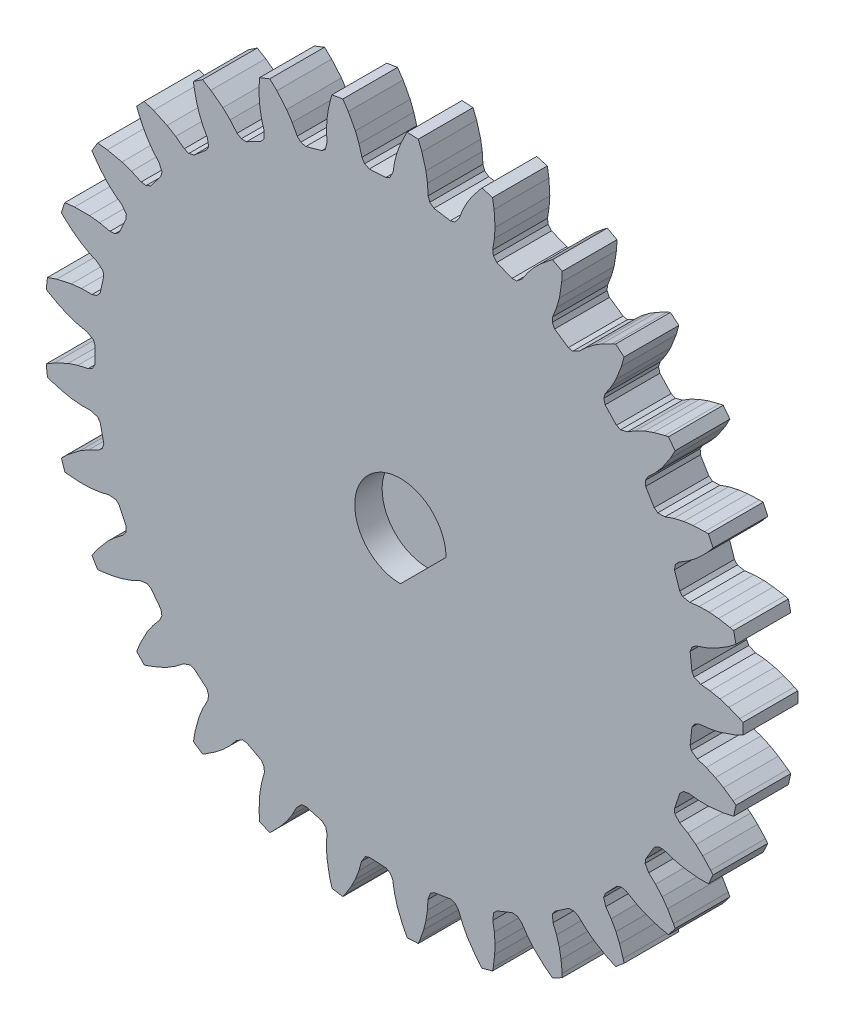
SolidWorks part; units mm, degrees
ref_plane "Front Plane" through (0, 0, 0) normal (0, 0, 1) x (1, 0, 0)
ref_plane "Top Plane" through (0, 0, 0) normal (0, 1, 0) x (1, 0, 0)
ref_plane "Right Plane" through (0, 0, 0) normal (1, 0, 0) x (0, 0, -1)
sketch "Model" plane through (0, 0, 0) normal (0, 0, 1) x (1, 0, 0)
  line L0 (37.4518, 6.9732) -> (36.9039, 6.5756)
  line L1 (36.9039, 6.5756) -> (36.3766, 6.2256)
  line L2 (36.3766, 6.2256) -> (35.8965, 5.9351)
  line L3 (35.8965, 5.9351) -> (35.4485, 5.6891)
  line L4 (35.4485, 5.6891) -> (35.0459, 5.4897)
  line L5 (35.0459, 5.4897) -> (34.6978, 5.3351)
  line L6 (34.6978, 5.3351) -> (34.3958, 5.2157)
  line L7 (34.3958, 5.2157) -> (34.1521, 5.1308)
  line L8 (34.1521, 5.1308) -> (33.7601, 5.0172)
  line L9 (33.7601, 5.0172) -> (33.6027, 4.9652)
  line L10 (33.6027, 4.9652) -> (33.4624, 4.9092)
  line L11 (33.4624, 4.9092) -> (33.3391, 4.8498)
  line L12 (33.3391, 4.8498) -> (33.233, 4.7877)
  line L13 (33.233, 4.7877) -> (33.144, 4.7237)
  line L14 (33.144, 4.7237) -> (33.0723, 4.6583)
  line L15 (33.0723, 4.6583) -> (33.0179, 4.5924)
  line L16 (33.0179, 4.5924) -> (32.9808, 4.5265)
  line L17 (32.9808, 4.5265) -> (32.9609, 4.4614)
  line L18 (32.9609, 4.4614) -> (32.96, 4.3823)
  line L19 (32.96, 4.3823) -> (33.0551, 3.595)
  line L20 (33.0551, 3.595) -> (33.1315, 2.8056)
  line L21 (33.1315, 2.8056) -> (33.1493, 2.7285)
  line L22 (33.1493, 2.7285) -> (33.1828, 2.6692)
  line L23 (33.1828, 2.6692) -> (33.2332, 2.6129)
  line L24 (33.2332, 2.6129) -> (33.3005, 2.5602)
  line L25 (33.3005, 2.5602) -> (33.3845, 2.5117)
  line L26 (33.3845, 2.5117) -> (33.4852, 2.4684)
  line L27 (33.4852, 2.4684) -> (33.6022, 2.4305)
  line L28 (33.6022, 2.4305) -> (33.7354, 2.399)
  line L29 (33.7354, 2.399) -> (33.8845, 2.3745)
  line L30 (33.8845, 2.3745) -> (34.0494, 2.3575)
  line L31 (34.0494, 2.3575) -> (34.4566, 2.3309)
  line L32 (34.4566, 2.3309) -> (34.7129, 2.3003)
  line L33 (34.7129, 2.3003) -> (35.0334, 2.2487)
  line L34 (35.0334, 2.2487) -> (35.4067, 2.1725)
  line L35 (35.4067, 2.1725) -> (35.8427, 2.0643)
  line L36 (35.8427, 2.0643) -> (36.3332, 1.9204)
  line L37 (36.3332, 1.9204) -> (36.8645, 1.7399)
  line L38 (36.8645, 1.7399) -> (37.4546, 1.5114)
  line L39 (37.4546, 1.5114) -> (38.0752, 1.2408)
  line L40 (38.0752, 1.2408) -> (38.7391, 0.9176)
  line L41 (38.7391, -0.9176) -> (38.0752, -1.2408)
  line L42 (38.0752, -1.2408) -> (37.4546, -1.5114)
  line L43 (37.4546, -1.5114) -> (36.8645, -1.7399)
  line L44 (36.8645, -1.7399) -> (36.3332, -1.9204)
  line L45 (36.3332, -1.9204) -> (35.8427, -2.0643)
  line L46 (35.8427, -2.0643) -> (35.4067, -2.1725)
  line L47 (35.4067, -2.1725) -> (35.0334, -2.2487)
  line L48 (35.0334, -2.2487) -> (34.7129, -2.3003)
  line L49 (34.7129, -2.3003) -> (34.4566, -2.3309)
  line L50 (34.4566, -2.3309) -> (34.0494, -2.3575)
  line L51 (34.0494, -2.3575) -> (33.8845, -2.3745)
  line L52 (33.8845, -2.3745) -> (33.7354, -2.399)
  line L53 (33.7354, -2.399) -> (33.6022, -2.4305)
  line L54 (33.6022, -2.4305) -> (33.4852, -2.4684)
  line L55 (33.4852, -2.4684) -> (33.3845, -2.5117)
  line L56 (33.3845, -2.5117) -> (33.3005, -2.5602)
  line L57 (33.3005, -2.5602) -> (33.2332, -2.6129)
  line L58 (33.2332, -2.6129) -> (33.1828, -2.6692)
  line L59 (33.1828, -2.6692) -> (33.1493, -2.7285)
  line L60 (33.1493, -2.7285) -> (33.1315, -2.8056)
  line L61 (33.1315, -2.8056) -> (33.0551, -3.595)
  line L62 (33.0551, -3.595) -> (32.96, -4.3823)
  line L63 (32.96, -4.3823) -> (32.9609, -4.4614)
  line L64 (32.9609, -4.4614) -> (32.9808, -4.5265)
  line L65 (32.9808, -4.5265) -> (33.0179, -4.5924)
  line L66 (33.0179, -4.5924) -> (33.0723, -4.6583)
  line L67 (33.0723, -4.6583) -> (33.144, -4.7237)
  line L68 (33.144, -4.7237) -> (33.233, -4.7877)
  line L69 (33.233, -4.7877) -> (33.3391, -4.8498)
  line L70 (33.3391, -4.8498) -> (33.4624, -4.9092)
  line L71 (33.4624, -4.9092) -> (33.6027, -4.9652)
  line L72 (33.6027, -4.9652) -> (33.7601, -5.0172)
  line L73 (33.7601, -5.0172) -> (34.1521, -5.1308)
  line L74 (34.1521, -5.1308) -> (34.3958, -5.2157)
  line L75 (34.3958, -5.2157) -> (34.6978, -5.3351)
  line L76 (34.6978, -5.3351) -> (35.0459, -5.4897)
  line L77 (35.0459, -5.4897) -> (35.4485, -5.6891)
  line L78 (35.4485, -5.6891) -> (35.8965, -5.9351)
  line L79 (35.8965, -5.9351) -> (36.3766, -6.2256)
  line L80 (36.3766, -6.2256) -> (36.9039, -6.5756)
  line L81 (36.9039, -6.5756) -> (37.4518, -6.9732)
  line L82 (37.4518, -6.9732) -> (38.0307, -7.4316)
  line L83 (37.6362, -9.2239) -> (36.9183, -9.3969)
  line L84 (36.9183, -9.3969) -> (36.2541, -9.5277)
  line L85 (36.2541, -9.5277) -> (35.6286, -9.624)
  line L86 (35.6286, -9.624) -> (35.0709, -9.686)
  line L87 (35.0709, -9.686) -> (34.561, -9.7211)
  line L88 (34.561, -9.7211) -> (34.1119, -9.7331)
  line L89 (34.1119, -9.7331) -> (33.731, -9.7272)
  line L90 (33.731, -9.7272) -> (33.4068, -9.7088)
  line L91 (33.4068, -9.7088) -> (33.1499, -9.6835)
  line L92 (33.1499, -9.6835) -> (32.7466, -9.622)
  line L93 (32.7466, -9.622) -> (32.5819, -9.6031)
  line L94 (32.5819, -9.6031) -> (32.431, -9.595)
  line L95 (32.431, -9.595) -> (32.2941, -9.5971)
  line L96 (32.2941, -9.5971) -> (32.1717, -9.609)
  line L97 (32.1717, -9.609) -> (32.0641, -9.6297)
  line L98 (32.0641, -9.6297) -> (31.9716, -9.659)
  line L99 (31.9716, -9.659) -> (31.8946, -9.6959)
  line L100 (31.8946, -9.6959) -> (31.8332, -9.7402)
  line L101 (31.8332, -9.7402) -> (31.7878, -9.7908)
  line L102 (31.7878, -9.7908) -> (31.7538, -9.8623)
  line L103 (31.7538, -9.8623) -> (31.5095, -10.6168)
  line L104 (31.5095, -10.6168) -> (31.2474, -11.3653)
  line L105 (31.2474, -11.3653) -> (31.2312, -11.4428)
  line L106 (31.2312, -11.4428) -> (31.2367, -11.5106)
  line L107 (31.2367, -11.5106) -> (31.2588, -11.5829)
  line L108 (31.2588, -11.5829) -> (31.2977, -11.6589)
  line L109 (31.2977, -11.6589) -> (31.3536, -11.7382)
  line L110 (31.3536, -11.7382) -> (31.4268, -11.8199)
  line L111 (31.4268, -11.8199) -> (31.5171, -11.9033)
  line L112 (31.5171, -11.9033) -> (31.6247, -11.9878)
  line L113 (31.6247, -11.9878) -> (31.7498, -12.0727)
  line L114 (31.7498, -12.0727) -> (31.8923, -12.1574)
  line L115 (31.8923, -12.1574) -> (32.2506, -12.3525)
  line L116 (32.2506, -12.3525) -> (32.4704, -12.4879)
  line L117 (32.4704, -12.4879) -> (32.7397, -12.6693)
  line L118 (32.7397, -12.6693) -> (33.0464, -12.8952)
  line L119 (33.0464, -12.8952) -> (33.3967, -13.1765)
  line L120 (33.3967, -13.1765) -> (33.7814, -13.513)
  line L121 (33.7814, -13.513) -> (34.1879, -13.9)
  line L122 (34.1879, -13.9) -> (34.6275, -14.3551)
  line L123 (34.6275, -14.3551) -> (35.0772, -14.8612)
  line L124 (35.0772, -14.8612) -> (35.544, -15.4333)
  line L125 (34.7734, -17.0989) -> (34.0351, -17.1135)
  line L126 (34.0351, -17.1135) -> (33.3583, -17.0985)
  line L127 (33.3583, -17.0985) -> (32.7268, -17.058)
  line L128 (32.7268, -17.058) -> (32.1687, -16.9988)
  line L129 (32.1687, -16.9988) -> (31.6632, -16.9235)
  line L130 (31.6632, -16.9235) -> (31.222, -16.8386)
  line L131 (31.222, -16.8386) -> (30.8513, -16.751)
  line L132 (30.8513, -16.751) -> (30.5387, -16.6633)
  line L133 (30.5387, -16.6633) -> (30.2932, -16.5834)
  line L134 (30.2932, -16.5834) -> (29.9125, -16.4366)
  line L135 (29.9125, -16.4366) -> (29.7557, -16.3828)
  line L136 (29.7557, -16.3828) -> (29.6101, -16.3424)
  line L137 (29.6101, -16.3424) -> (29.476, -16.315)
  line L138 (29.476, -16.315) -> (29.3539, -16.3003)
  line L139 (29.3539, -16.3003) -> (29.2443, -16.2974)
  line L140 (29.2443, -16.2974) -> (29.1477, -16.3061)
  line L141 (29.1477, -16.3061) -> (29.0645, -16.3256)
  line L142 (29.0645, -16.3256) -> (28.9951, -16.3556)
  line L143 (28.9951, -16.3556) -> (28.9399, -16.3953)
  line L144 (28.9399, -16.3953) -> (28.8913, -16.4578)
  line L145 (28.8913, -16.4578) -> (28.4905, -17.1422)
  line L146 (28.4905, -17.1422) -> (28.0736, -17.8168)
  line L147 (28.0736, -17.8168) -> (28.0411, -17.889)
  line L148 (28.0411, -17.889) -> (28.032, -17.9564)
  line L149 (28.032, -17.9564) -> (28.038, -18.0318)
  line L150 (28.038, -18.0318) -> (28.0597, -18.1144)
  line L151 (28.0597, -18.1144) -> (28.0972, -18.2039)
  line L152 (28.0972, -18.2039) -> (28.1511, -18.2993)
  line L153 (28.1511, -18.2993) -> (28.2213, -18.4003)
  line L154 (28.2213, -18.4003) -> (28.3083, -18.506)
  line L155 (28.3083, -18.506) -> (28.4122, -18.6157)
  line L156 (28.4122, -18.6157) -> (28.5332, -18.729)
  line L157 (28.5332, -18.729) -> (28.8412, -18.9966)
  line L158 (28.8412, -18.9966) -> (29.0268, -19.1761)
  line L159 (29.0268, -19.1761) -> (29.2507, -19.4112)
  line L160 (29.2507, -19.4112) -> (29.5017, -19.6977)
  line L161 (29.5017, -19.6977) -> (29.7834, -20.0477)
  line L162 (29.7834, -20.0477) -> (30.0867, -20.4591)
  line L163 (30.0867, -20.4591) -> (30.4005, -20.9244)
  line L164 (30.4005, -20.9244) -> (30.7321, -21.4634)
  line L165 (30.7321, -21.4634) -> (31.0624, -22.0543)
  line L166 (31.0624, -22.0543) -> (31.3953, -22.7134)
  line L167 (30.2846, -24.1744) -> (29.5605, -24.03)
  line L168 (29.5605, -24.03) -> (28.9027, -23.8698)
  line L169 (28.9027, -23.8698) -> (28.2947, -23.6945)
  line L170 (28.2947, -23.6945) -> (27.7624, -23.5167)
  line L171 (27.7624, -23.5167) -> (27.2849, -23.3345)
  line L172 (27.2849, -23.3345) -> (26.8723, -23.1567)
  line L173 (26.8723, -23.1567) -> (26.529, -22.9915)
  line L174 (26.529, -22.9915) -> (26.2426, -22.8386)
  line L175 (26.2426, -22.8386) -> (26.0201, -22.7078)
  line L176 (26.0201, -22.7078) -> (25.6798, -22.4826)
  line L177 (25.6798, -22.4826) -> (25.5382, -22.3963)
  line L178 (25.5382, -22.3963) -> (25.4047, -22.3256)
  line L179 (25.4047, -22.3256) -> (25.2796, -22.2701)
  line L180 (25.2796, -22.2701) -> (25.1636, -22.2294)
  line L181 (25.1636, -22.2294) -> (25.0572, -22.203)
  line L182 (25.0572, -22.203) -> (24.9609, -22.1908)
  line L183 (24.9609, -22.1908) -> (24.8755, -22.192)
  line L184 (24.8755, -22.192) -> (24.8013, -22.2064)
  line L185 (24.8013, -22.2064) -> (24.7387, -22.2332)
  line L186 (24.7387, -22.2332) -> (24.6779, -22.2838)
  line L187 (24.6779, -22.2838) -> (24.1394, -22.866)
  line L188 (24.1394, -22.866) -> (23.5872, -23.4353)
  line L189 (23.5872, -23.4353) -> (23.54, -23.4988)
  line L190 (23.54, -23.4988) -> (23.5165, -23.5627)
  line L191 (23.5165, -23.5627) -> (23.5062, -23.6376)
  line L192 (23.5062, -23.6376) -> (23.5096, -23.7229)
  line L193 (23.5096, -23.7229) -> (23.527, -23.8184)
  line L194 (23.527, -23.8184) -> (23.5592, -23.9232)
  line L195 (23.5592, -23.9232) -> (23.606, -24.0369)
  line L196 (23.606, -24.0369) -> (23.6682, -24.1587)
  line L197 (23.6682, -24.1587) -> (23.7461, -24.2883)
  line L198 (23.7461, -24.2883) -> (23.8399, -24.4249)
  line L199 (23.8399, -24.4249) -> (24.0832, -24.7525)
  line L200 (24.0832, -24.7525) -> (24.2259, -24.9677)
  line L201 (24.2259, -24.9677) -> (24.394, -25.2454)
  line L202 (24.394, -25.2454) -> (24.5776, -25.5792)
  line L203 (24.5776, -25.5792) -> (24.7774, -25.9816)
  line L204 (24.7774, -25.9816) -> (24.9852, -26.4485)
  line L205 (24.9852, -26.4485) -> (25.1916, -26.9704)
  line L206 (25.1916, -26.9704) -> (25.3996, -27.568)
  line L207 (25.3996, -27.568) -> (25.5951, -28.2162)
  line L208 (25.5951, -28.2162) -> (25.7785, -28.9314)
  line L209 (24.3798, -30.1195) -> (23.7037, -29.8228)
  line L210 (23.7037, -29.8228) -> (23.0957, -29.525)
  line L211 (23.0957, -29.525) -> (22.5395, -29.2231)
  line L212 (22.5395, -29.2231) -> (22.058, -28.935)
  line L213 (22.058, -28.935) -> (21.6308, -28.6544)
  line L214 (21.6308, -28.6544) -> (21.266, -28.392)
  line L215 (21.266, -28.392) -> (20.9663, -28.1569)
  line L216 (20.9663, -28.1569) -> (20.7194, -27.946)
  line L217 (20.7194, -27.946) -> (20.5302, -27.7705)
  line L218 (20.5302, -27.7705) -> (20.2463, -27.4774)
  line L219 (20.2463, -27.4774) -> (20.1266, -27.3627)
  line L220 (20.1266, -27.3627) -> (20.0114, -27.2649)
  line L221 (20.0114, -27.2649) -> (19.9012, -27.1838)
  line L222 (19.9012, -27.1838) -> (19.7966, -27.1191)
  line L223 (19.7966, -27.1191) -> (19.6983, -27.0705)
  line L224 (19.6983, -27.0705) -> (19.607, -27.0378)
  line L225 (19.607, -27.0378) -> (19.5233, -27.0206)
  line L226 (19.5233, -27.0206) -> (19.4477, -27.0187)
  line L227 (19.4477, -27.0187) -> (19.3809, -27.0315)
  line L228 (19.3809, -27.0315) -> (19.3106, -27.0679)
  line L229 (19.3106, -27.0679) -> (18.6595, -27.5207)
  line L230 (18.6595, -27.5207) -> (17.9978, -27.9579)
  line L231 (17.9978, -27.9579) -> (17.9381, -28.0098)
  line L232 (17.9381, -28.0098) -> (17.9014, -28.0671)
  line L233 (17.9014, -28.0671) -> (17.8752, -28.1381)
  line L234 (17.8752, -28.1381) -> (17.8602, -28.2222)
  line L235 (17.8602, -28.2222) -> (17.8567, -28.3191)
  line L236 (17.8567, -28.3191) -> (17.8656, -28.4284)
  line L237 (17.8656, -28.4284) -> (17.8869, -28.5495)
  line L238 (17.8869, -28.5495) -> (17.9215, -28.6819)
  line L239 (17.9215, -28.6819) -> (17.9697, -28.8251)
  line L240 (17.9697, -28.8251) -> (18.0319, -28.9788)
  line L241 (18.0319, -28.9788) -> (18.1991, -29.351)
  line L242 (18.1991, -29.351) -> (18.2922, -29.5918)
  line L243 (18.2922, -29.5918) -> (18.3967, -29.8992)
  line L244 (18.3967, -29.8992) -> (18.5042, -30.2646)
  line L245 (18.5042, -30.2646) -> (18.6129, -30.7006)
  line L246 (18.6129, -30.7006) -> (18.7154, -31.2013)
  line L247 (18.7154, -31.2013) -> (18.8048, -31.7553)
  line L248 (18.8048, -31.7553) -> (18.8794, -32.3837)
  line L249 (18.8794, -32.3837) -> (18.9311, -33.0587)
  line L250 (18.9311, -33.0587) -> (18.9564, -33.7967)
  line L251 (17.335, -34.6563) -> (16.7385, -34.2212)
  line L252 (16.7385, -34.2212) -> (16.2087, -33.7996)
  line L253 (16.2087, -33.7996) -> (15.7305, -33.3852)
  line L254 (15.7305, -33.3852) -> (15.3221, -33.0003)
  line L255 (15.3221, -33.0003) -> (14.9652, -32.6344)
  line L256 (14.9652, -32.6344) -> (14.6654, -32.2998)
  line L257 (14.6654, -32.2998) -> (14.4232, -32.0058)
  line L258 (14.4232, -32.0058) -> (14.2275, -31.7467)
  line L259 (14.2275, -31.7467) -> (14.0804, -31.5346)
  line L260 (14.0804, -31.5346) -> (13.8661, -31.1873)
  line L261 (13.8661, -31.1873) -> (13.7739, -31.0496)
  line L262 (13.7739, -31.0496) -> (13.6824, -30.9293)
  line L263 (13.6824, -30.9293) -> (13.5922, -30.8264)
  line L264 (13.5922, -30.8264) -> (13.5039, -30.7408)
  line L265 (13.5039, -30.7408) -> (13.4185, -30.6722)
  line L266 (13.4185, -30.6722) -> (13.3362, -30.6206)
  line L267 (13.3362, -30.6206) -> (13.2582, -30.5858)
  line L268 (13.2582, -30.5858) -> (13.1848, -30.5677)
  line L269 (13.1848, -30.5677) -> (13.1168, -30.5659)
  line L270 (13.1168, -30.5659) -> (13.0403, -30.5862)
  line L271 (13.0403, -30.5862) -> (12.3071, -30.8885)
  line L272 (12.3071, -30.8885) -> (11.5669, -31.1733)
  line L273 (11.5669, -31.1733) -> (11.4974, -31.2111)
  line L274 (11.4974, -31.2111) -> (11.4493, -31.2592)
  line L275 (11.4493, -31.2592) -> (11.4084, -31.3228)
  line L276 (11.4084, -31.3228) -> (11.3757, -31.4018)
  line L277 (11.3757, -31.4018) -> (11.3515, -31.4957)
  line L278 (11.3515, -31.4957) -> (11.3366, -31.6043)
  line L279 (11.3366, -31.6043) -> (11.3314, -31.7272)
  line L280 (11.3314, -31.7272) -> (11.3367, -31.8639)
  line L281 (11.3367, -31.8639) -> (11.353, -32.0142)
  line L282 (11.353, -32.0142) -> (11.3808, -32.1776)
  line L283 (11.3808, -32.1776) -> (11.464, -32.5771)
  line L284 (11.464, -32.5771) -> (11.5031, -32.8322)
  line L285 (11.5031, -32.8322) -> (11.5391, -33.1549)
  line L286 (11.5391, -33.1549) -> (11.5656, -33.5349)
  line L287 (11.5656, -33.5349) -> (11.578, -33.984)
  line L288 (11.578, -33.984) -> (11.5705, -34.4951)
  line L289 (11.5705, -34.4951) -> (11.5387, -35.0553)
  line L290 (11.5387, -35.0553) -> (11.4765, -35.6851)
  line L291 (11.4765, -35.6851) -> (11.3818, -36.3554)
  line L292 (11.3818, -36.3554) -> (11.248, -37.0816)
  line L293 (9.4796, -37.5726) -> (8.9906, -37.0194)
  line L294 (8.9906, -37.0194) -> (8.5639, -36.4938)
  line L295 (8.5639, -36.4938) -> (8.1859, -35.9862)
  line L296 (8.1859, -35.9862) -> (7.8698, -35.5226)
  line L297 (7.8698, -35.5226) -> (7.5999, -35.0885)
  line L298 (7.5999, -35.0885) -> (7.379, -34.6973)
  line L299 (7.379, -34.6973) -> (7.2057, -34.3581)
  line L300 (7.2057, -34.3581) -> (7.0702, -34.063)
  line L301 (7.0702, -34.063) -> (6.9722, -33.8242)
  line L302 (6.9722, -33.8242) -> (6.8376, -33.439)
  line L303 (6.8376, -33.439) -> (6.7771, -33.2847)
  line L304 (6.7771, -33.2847) -> (6.7136, -33.1475)
  line L305 (6.7136, -33.1475) -> (6.6476, -33.0276)
  line L306 (6.6476, -33.0276) -> (6.5799, -32.925)
  line L307 (6.5799, -32.925) -> (6.5111, -32.8396)
  line L308 (6.5111, -32.8396) -> (6.4419, -32.7716)
  line L309 (6.4419, -32.7716) -> (6.3732, -32.7209)
  line L310 (6.3732, -32.7209) -> (6.3054, -32.6874)
  line L311 (6.3054, -32.6874) -> (6.2394, -32.671)
  line L312 (6.2394, -32.671) -> (6.1603, -32.6744)
  line L313 (6.1603, -32.6744) -> (5.3793, -32.812)
  line L314 (5.3793, -32.812) -> (4.5952, -32.931)
  line L315 (4.5952, -32.931) -> (4.5191, -32.953)
  line L316 (4.5191, -32.953) -> (4.4618, -32.9896)
  line L317 (4.4618, -32.9896) -> (4.4082, -33.043)
  line L318 (4.4082, -33.043) -> (4.3593, -33.1131)
  line L319 (4.3593, -33.1131) -> (4.3154, -33.1996)
  line L320 (4.3154, -33.1996) -> (4.2776, -33.3025)
  line L321 (4.2776, -33.3025) -> (4.2461, -33.4213)
  line L322 (4.2461, -33.4213) -> (4.2219, -33.556)
  line L323 (4.2219, -33.556) -> (4.2055, -33.7063)
  line L324 (4.2055, -33.7063) -> (4.1974, -33.8718)
  line L325 (4.1974, -33.8718) -> (4.1929, -34.2798)
  line L326 (4.1929, -34.2798) -> (4.1763, -34.5374)
  line L327 (4.1763, -34.5374) -> (4.142, -34.8603)
  line L328 (4.142, -34.8603) -> (4.0862, -35.2371)
  line L329 (4.0862, -35.2371) -> (4.0017, -35.6784)
  line L330 (4.0017, -35.6784) -> (3.8846, -36.1759)
  line L331 (3.8846, -36.1759) -> (3.7331, -36.7162)
  line L332 (3.7331, -36.7162) -> (3.537, -37.3179)
  line L333 (3.537, -37.3179) -> (3.3004, -37.9522)
  line L334 (3.3004, -37.9522) -> (3.0136, -38.6326)
  line L335 (1.181, -38.732) -> (0.8223, -38.0866)
  line L336 (0.8223, -38.0866) -> (0.5186, -37.4815)
  line L337 (0.5186, -37.4815) -> (0.2585, -36.9046)
  line L338 (0.2585, -36.9046) -> (0.0495, -36.3838)
  line L339 (0.0495, -36.3838) -> (-0.1208, -35.9019)
  line L340 (-0.1208, -35.9019) -> (-0.2524, -35.4724)
  line L341 (-0.2524, -35.4724) -> (-0.3487, -35.1038)
  line L342 (-0.3487, -35.1038) -> (-0.4176, -34.7865)
  line L343 (-0.4176, -34.7865) -> (-0.462, -34.5322)
  line L344 (-0.462, -34.5322) -> (-0.5107, -34.1271)
  line L345 (-0.5107, -34.1271) -> (-0.5365, -33.9634)
  line L346 (-0.5365, -33.9634) -> (-0.5691, -33.8158)
  line L347 (-0.5691, -33.8158) -> (-0.6077, -33.6845)
  line L348 (-0.6077, -33.6845) -> (-0.6519, -33.5697)
  line L349 (-0.6519, -33.5697) -> (-0.7006, -33.4716)
  line L350 (-0.7006, -33.4716) -> (-0.7536, -33.3903)
  line L351 (-0.7536, -33.3903) -> (-0.8098, -33.3259)
  line L352 (-0.8098, -33.3259) -> (-0.8688, -33.2787)
  line L353 (-0.8688, -33.2787) -> (-0.9298, -33.2484)
  line L354 (-0.9298, -33.2484) -> (-1.0078, -33.2348)
  line L355 (-1.0078, -33.2348) -> (-1.8001, -33.2012)
  line L356 (-1.8001, -33.2012) -> (-2.5914, -33.1489)
  line L357 (-2.5914, -33.1489) -> (-2.6704, -33.154)
  line L358 (-2.6704, -33.154) -> (-2.7343, -33.1775)
  line L359 (-2.7343, -33.1775) -> (-2.7981, -33.2181)
  line L360 (-2.7981, -33.2181) -> (-2.8609, -33.276)
  line L361 (-2.8609, -33.276) -> (-2.9224, -33.3511)
  line L362 (-2.9224, -33.3511) -> (-2.9815, -33.4434)
  line L363 (-2.9815, -33.4434) -> (-3.0378, -33.5527)
  line L364 (-3.0378, -33.5527) -> (-3.0904, -33.6791)
  line L365 (-3.0904, -33.6791) -> (-3.1387, -33.8223)
  line L366 (-3.1387, -33.8223) -> (-3.1821, -33.9823)
  line L367 (-3.1821, -33.9823) -> (-3.2743, -34.3798)
  line L368 (-3.2743, -34.3798) -> (-3.3459, -34.6277)
  line L369 (-3.3459, -34.6277) -> (-3.4487, -34.9357)
  line L370 (-3.4487, -34.9357) -> (-3.5843, -35.2917)
  line L371 (-3.5843, -35.2917) -> (-3.7616, -35.7045)
  line L372 (-3.7616, -35.7045) -> (-3.983, -36.1652)
  line L373 (-3.983, -36.1652) -> (-4.2471, -36.6603)
  line L374 (-4.2471, -36.6603) -> (-4.568, -37.2058)
  line L375 (-4.568, -37.2058) -> (-4.9354, -37.7744)
  line L376 (-4.9354, -37.7744) -> (-5.3618, -38.3772)
  line L377 (-7.1728, -38.0803) -> (-7.3844, -37.3729)
  line L378 (-7.3844, -37.3729) -> (-7.551, -36.7167)
  line L379 (-7.551, -36.7167) -> (-7.6809, -36.0974)
  line L380 (-7.6809, -36.0974) -> (-7.7731, -35.5438)
  line L381 (-7.7731, -35.5438) -> (-7.8358, -35.0366)
  line L382 (-7.8358, -35.0366) -> (-7.872, -34.5888)
  line L383 (-7.872, -34.5888) -> (-7.8868, -34.2081)
  line L384 (-7.8868, -34.2081) -> (-7.8859, -33.8834)
  line L385 (-7.8859, -33.8834) -> (-7.8746, -33.6256)
  line L386 (-7.8746, -33.6256) -> (-7.835, -33.2195)
  line L387 (-7.835, -33.2195) -> (-7.8251, -33.054)
  line L388 (-7.8251, -33.054) -> (-7.8252, -32.9029)
  line L389 (-7.8252, -32.9029) -> (-7.8347, -32.7663)
  line L390 (-7.8347, -32.7663) -> (-7.8531, -32.6448)
  line L391 (-7.8531, -32.6448) -> (-7.8797, -32.5384)
  line L392 (-7.8797, -32.5384) -> (-7.9139, -32.4476)
  line L393 (-7.9139, -32.4476) -> (-7.955, -32.3727)
  line L394 (-7.955, -32.3727) -> (-8.0025, -32.3139)
  line L395 (-8.0025, -32.3139) -> (-8.0555, -32.2712)
  line L396 (-8.0555, -32.2712) -> (-8.1287, -32.2411)
  line L397 (-8.1287, -32.2411) -> (-8.8953, -32.038)
  line L398 (-8.8953, -32.038) -> (-9.6569, -31.8168)
  line L399 (-9.6569, -31.8168) -> (-9.7351, -31.8049)
  line L400 (-9.7351, -31.8049) -> (-9.8026, -31.8141)
  line L401 (-9.8026, -31.8141) -> (-9.8736, -31.84)
  line L402 (-9.8736, -31.84) -> (-9.9474, -31.883)
  line L403 (-9.9474, -31.883) -> (-10.0236, -31.9431)
  line L404 (-10.0236, -31.9431) -> (-10.1011, -32.0206)
  line L405 (-10.1011, -32.0206) -> (-10.1796, -32.1153)
  line L406 (-10.1796, -32.1153) -> (-10.2581, -32.2273)
  line L407 (-10.2581, -32.2273) -> (-10.3361, -32.3568)
  line L408 (-10.3361, -32.3568) -> (-10.4129, -32.5037)
  line L409 (-10.4129, -32.5037) -> (-10.5884, -32.8721)
  line L410 (-10.5884, -32.8721) -> (-10.7116, -33.0989)
  line L411 (-10.7116, -33.0989) -> (-10.8783, -33.3776)
  line L412 (-10.8783, -33.3776) -> (-11.0872, -33.6961)
  line L413 (-11.0872, -33.6961) -> (-11.3491, -34.0611)
  line L414 (-11.3491, -34.0611) -> (-11.6643, -34.4635)
  line L415 (-11.6643, -34.4635) -> (-12.0287, -34.8902)
  line L416 (-12.0287, -34.8902) -> (-12.4593, -35.3539)
  line L417 (-12.4593, -35.3539) -> (-12.9404, -35.8303)
  line L418 (-12.9404, -35.8303) -> (-13.4864, -36.3274)
  line L419 (-15.1913, -35.6481) -> (-15.2458, -34.9117)
  line L420 (-15.2458, -34.9117) -> (-15.2675, -34.2351)
  line L421 (-15.2675, -34.2351) -> (-15.2612, -33.6023)
  line L422 (-15.2612, -33.6023) -> (-15.2323, -33.0419)
  line L423 (-15.2323, -33.0419) -> (-15.1844, -32.533)
  line L424 (-15.1844, -32.533) -> (-15.1235, -32.0879)
  line L425 (-15.1235, -32.0879) -> (-15.0562, -31.7129)
  line L426 (-15.0562, -31.7129) -> (-14.9855, -31.396)
  line L427 (-14.9855, -31.396) -> (-14.919, -31.1466)
  line L428 (-14.919, -31.1466) -> (-14.7931, -30.7585)
  line L429 (-14.7931, -30.7585) -> (-14.7478, -30.599)
  line L430 (-14.7478, -30.599) -> (-14.7154, -30.4514)
  line L431 (-14.7154, -30.4514) -> (-14.6953, -30.316)
  line L432 (-14.6953, -30.316) -> (-14.6872, -30.1934)
  line L433 (-14.6872, -30.1934) -> (-14.6902, -30.0838)
  line L434 (-14.6902, -30.0838) -> (-14.7042, -29.9878)
  line L435 (-14.7042, -29.9878) -> (-14.7282, -29.9058)
  line L436 (-14.7282, -29.9058) -> (-14.7619, -29.8381)
  line L437 (-14.7619, -29.8381) -> (-14.8045, -29.785)
  line L438 (-14.8045, -29.785) -> (-14.8696, -29.7399)
  line L439 (-14.8696, -29.7399) -> (-15.5746, -29.3768)
  line L440 (-15.5746, -29.3768) -> (-16.2708, -28.997)
  line L441 (-16.2708, -28.997) -> (-16.3447, -28.9685)
  line L442 (-16.3447, -28.9685) -> (-16.4125, -28.963)
  line L443 (-16.4125, -28.963) -> (-16.4874, -28.9731)
  line L444 (-16.4874, -28.9731) -> (-16.5687, -28.9992)
  line L445 (-16.5687, -28.9992) -> (-16.656, -29.0416)
  line L446 (-16.656, -29.0416) -> (-16.7484, -29.1006)
  line L447 (-16.7484, -29.1006) -> (-16.8454, -29.1761)
  line L448 (-16.8454, -29.1761) -> (-16.9462, -29.2687)
  line L449 (-16.9462, -29.2687) -> (-17.0502, -29.3784)
  line L450 (-17.0502, -29.3784) -> (-17.1568, -29.5053)
  line L451 (-17.1568, -29.5053) -> (-17.4073, -29.8274)
  line L452 (-17.4073, -29.8274) -> (-17.5765, -30.0224)
  line L453 (-17.5765, -30.0224) -> (-17.7991, -30.2587)
  line L454 (-17.7991, -30.2587) -> (-18.0716, -30.5249)
  line L455 (-18.0716, -30.5249) -> (-18.4059, -30.8251)
  line L456 (-18.4059, -30.8251) -> (-18.8002, -31.1502)
  line L457 (-18.8002, -31.1502) -> (-19.2478, -31.4887)
  line L458 (-19.2478, -31.4887) -> (-19.7681, -31.849)
  line L459 (-19.7681, -31.849) -> (-20.3403, -32.2108)
  line L460 (-20.3403, -32.2108) -> (-20.9804, -32.5789)
  line L461 (-22.4994, -31.549) -> (-22.3944, -30.8181)
  line L462 (-22.3944, -30.8181) -> (-22.27, -30.1526)
  line L463 (-22.27, -30.1526) -> (-22.1279, -29.536)
  line L464 (-22.1279, -29.536) -> (-21.9792, -28.9949)
  line L465 (-21.9792, -28.9949) -> (-21.8231, -28.5082)
  line L466 (-21.8231, -28.5082) -> (-21.6679, -28.0865)
  line L467 (-21.6679, -28.0865) -> (-21.5215, -27.7349)
  line L468 (-21.5215, -27.7349) -> (-21.3844, -27.4406)
  line L469 (-21.3844, -27.4406) -> (-21.2658, -27.2113)
  line L470 (-21.2658, -27.2113) -> (-21.0594, -26.8593)
  line L471 (-21.0594, -26.8593) -> (-20.9809, -26.7133)
  line L472 (-20.9809, -26.7133) -> (-20.9175, -26.5761)
  line L473 (-20.9175, -26.5761) -> (-20.8688, -26.4482)
  line L474 (-20.8688, -26.4482) -> (-20.8345, -26.3301)
  line L475 (-20.8345, -26.3301) -> (-20.8139, -26.2225)
  line L476 (-20.8139, -26.2225) -> (-20.8069, -26.1257)
  line L477 (-20.8069, -26.1257) -> (-20.8127, -26.0405)
  line L478 (-20.8127, -26.0405) -> (-20.8311, -25.9671)
  line L479 (-20.8311, -25.9671) -> (-20.8613, -25.9062)
  line L480 (-20.8613, -25.9062) -> (-20.9151, -25.8481)
  line L481 (-20.9151, -25.8481) -> (-21.5256, -25.3419)
  line L482 (-21.5256, -25.3419) -> (-22.1239, -24.8213)
  line L483 (-22.1239, -24.8213) -> (-22.1899, -24.7776)
  line L484 (-22.1899, -24.7776) -> (-22.2549, -24.7577)
  line L485 (-22.2549, -24.7577) -> (-22.3303, -24.7514)
  line L486 (-22.3303, -24.7514) -> (-22.4153, -24.7594)
  line L487 (-22.4153, -24.7594) -> (-22.5097, -24.782)
  line L488 (-22.5097, -24.782) -> (-22.6126, -24.8198)
  line L489 (-22.6126, -24.8198) -> (-22.7236, -24.8727)
  line L490 (-22.7236, -24.8727) -> (-22.8419, -24.9415)
  line L491 (-22.8419, -24.9415) -> (-22.9671, -25.0262)
  line L492 (-22.9671, -25.0262) -> (-23.0985, -25.1273)
  line L493 (-23.0985, -25.1273) -> (-23.4124, -25.388)
  line L494 (-23.4124, -25.388) -> (-23.6195, -25.542)
  line L495 (-23.6195, -25.542) -> (-23.8877, -25.725)
  line L496 (-23.8877, -25.725) -> (-24.2111, -25.9264)
  line L497 (-24.2111, -25.9264) -> (-24.6021, -26.1477)
  line L498 (-24.6021, -26.1477) -> (-25.0571, -26.3805)
  line L499 (-25.0571, -26.3805) -> (-25.567, -26.6148)
  line L500 (-25.567, -26.6148) -> (-26.1525, -26.8548)
  line L501 (-26.1525, -26.8548) -> (-26.7891, -27.0852)
  line L502 (-26.7891, -27.0852) -> (-27.4934, -27.307)
  line L503 (-28.7555, -25.9747) -> (-28.4958, -25.2835)
  line L504 (-28.4958, -25.2835) -> (-28.2313, -24.6603)
  line L505 (-28.2313, -24.6603) -> (-27.9599, -24.0886)
  line L506 (-27.9599, -24.0886) -> (-27.6983, -23.5921)
  line L507 (-27.6983, -23.5921) -> (-27.4413, -23.1504)
  line L508 (-27.4413, -23.1504) -> (-27.1991, -22.7719)
  line L509 (-27.1991, -22.7719) -> (-26.9805, -22.46)
  line L510 (-26.9805, -22.46) -> (-26.7833, -22.202)
  line L511 (-26.7833, -22.202) -> (-26.6183, -22.0036)
  line L512 (-26.6183, -22.0036) -> (-26.341, -21.7042)
  line L513 (-26.341, -21.7042) -> (-26.2329, -21.5785)
  line L514 (-26.2329, -21.5785) -> (-26.1415, -21.4581)
  line L515 (-26.1415, -21.4581) -> (-26.0665, -21.3437)
  line L516 (-26.0665, -21.3437) -> (-26.0076, -21.2357)
  line L517 (-26.0076, -21.2357) -> (-25.9643, -21.135)
  line L518 (-25.9643, -21.135) -> (-25.9367, -21.042)
  line L519 (-25.9367, -21.042) -> (-25.924, -20.9575)
  line L520 (-25.924, -20.9575) -> (-25.9262, -20.882)
  line L521 (-25.9262, -20.882) -> (-25.9426, -20.8159)
  line L522 (-25.9426, -20.8159) -> (-25.9827, -20.7477)
  line L523 (-25.9827, -20.7477) -> (-26.4701, -20.122)
  line L524 (-26.4701, -20.122) -> (-26.9425, -19.4851)
  line L525 (-26.9425, -19.4851) -> (-26.9976, -19.4282)
  line L526 (-26.9976, -19.4282) -> (-27.0568, -19.3947)
  line L527 (-27.0568, -19.3947) -> (-27.129, -19.3724)
  line L528 (-27.129, -19.3724) -> (-27.2138, -19.3619)
  line L529 (-27.2138, -19.3619) -> (-27.3108, -19.3637)
  line L530 (-27.3108, -19.3637) -> (-27.4195, -19.3785)
  line L531 (-27.4195, -19.3785) -> (-27.5392, -19.4063)
  line L532 (-27.5392, -19.4063) -> (-27.6696, -19.448)
  line L533 (-27.6696, -19.448) -> (-27.81, -19.5039)
  line L534 (-27.81, -19.5039) -> (-27.9601, -19.5744)
  line L535 (-27.9601, -19.5744) -> (-28.3227, -19.7614)
  line L536 (-28.3227, -19.7614) -> (-28.558, -19.8674)
  line L537 (-28.558, -19.8674) -> (-28.8594, -19.9884)
  line L538 (-28.8594, -19.9884) -> (-29.2184, -20.1155)
  line L539 (-29.2184, -20.1155) -> (-29.6478, -20.2476)
  line L540 (-29.6478, -20.2476) -> (-30.1423, -20.3772)
  line L541 (-30.1423, -20.3772) -> (-30.6906, -20.4964)
  line L542 (-30.6906, -20.4964) -> (-31.3141, -20.605)
  line L543 (-31.3141, -20.605) -> (-31.9853, -20.6931)
  line L544 (-31.9853, -20.6931) -> (-32.7208, -20.7584)
  line L545 (-33.667, -19.1858) -> (-33.2648, -18.5666)
  line L546 (-33.2648, -18.5666) -> (-32.8725, -18.0148)
  line L547 (-32.8725, -18.0148) -> (-32.4846, -17.5148)
  line L548 (-32.4846, -17.5148) -> (-32.1224, -17.0862)
  line L549 (-32.1224, -17.0862) -> (-31.7763, -16.7101)
  line L550 (-31.7763, -16.7101) -> (-31.4585, -16.3925)
  line L551 (-31.4585, -16.3925) -> (-31.178, -16.1348)
  line L552 (-31.178, -16.1348) -> (-30.9299, -15.9253)
  line L553 (-30.9299, -15.9253) -> (-30.7261, -15.767)
  line L554 (-30.7261, -15.767) -> (-30.3909, -15.5343)
  line L555 (-30.3909, -15.5343) -> (-30.2584, -15.4347)
  line L556 (-30.2584, -15.4347) -> (-30.1432, -15.3368)
  line L557 (-30.1432, -15.3368) -> (-30.0453, -15.2412)
  line L558 (-30.0453, -15.2412) -> (-29.9646, -15.1484)
  line L559 (-29.9646, -15.1484) -> (-29.9007, -15.0593)
  line L560 (-29.9007, -15.0593) -> (-29.8537, -14.9745)
  line L561 (-29.8537, -14.9745) -> (-29.8232, -14.8947)
  line L562 (-29.8232, -14.8947) -> (-29.8091, -14.8204)
  line L563 (-29.8091, -14.8204) -> (-29.8109, -14.7524)
  line L564 (-29.8109, -14.7524) -> (-29.8354, -14.6771)
  line L565 (-29.8354, -14.6771) -> (-30.1769, -13.9613)
  line L566 (-30.1769, -13.9613) -> (-30.5013, -13.2377)
  line L567 (-30.5013, -13.2377) -> (-30.5429, -13.1703)
  line L568 (-30.5429, -13.1703) -> (-30.5935, -13.1248)
  line L569 (-30.5935, -13.1248) -> (-30.6593, -13.0875)
  line L570 (-30.6593, -13.0875) -> (-30.7398, -13.0591)
  line L571 (-30.7398, -13.0591) -> (-30.835, -13.04)
  line L572 (-30.835, -13.04) -> (-30.9442, -13.031)
  line L573 (-30.9442, -13.031) -> (-31.0672, -13.0325)
  line L574 (-31.0672, -13.0325) -> (-31.2034, -13.0452)
  line L575 (-31.2034, -13.0452) -> (-31.3526, -13.0696)
  line L576 (-31.3526, -13.0696) -> (-31.5143, -13.1061)
  line L577 (-31.5143, -13.1061) -> (-31.9086, -13.2109)
  line L578 (-31.9086, -13.2109) -> (-32.1613, -13.2638)
  line L579 (-32.1613, -13.2638) -> (-32.4816, -13.3172)
  line L580 (-32.4816, -13.3172) -> (-32.8596, -13.3642)
  line L581 (-32.8596, -13.3642) -> (-33.3073, -13.4009)
  line L582 (-33.3073, -13.4009) -> (-33.8181, -13.4211)
  line L583 (-33.8181, -13.4211) -> (-34.3792, -13.4197)
  line L584 (-34.3792, -13.4197) -> (-35.0114, -13.3916)
  line L585 (-35.0114, -13.3916) -> (-35.6859, -13.3334)
  line L586 (-35.6859, -13.3334) -> (-36.4182, -13.239)
  line L587 (-37.0042, -11.4999) -> (-36.4783, -10.9816)
  line L588 (-36.4783, -10.9816) -> (-35.9766, -10.527)
  line L589 (-35.9766, -10.527) -> (-35.4903, -10.1221)
  line L590 (-35.4903, -10.1221) -> (-35.0444, -9.7814)
  line L591 (-35.0444, -9.7814) -> (-34.6256, -9.4884)
  line L592 (-34.6256, -9.4884) -> (-34.2469, -9.2467)
  line L593 (-34.2469, -9.2467) -> (-33.9176, -9.0553)
  line L594 (-33.9176, -9.0553) -> (-33.6303, -8.904)
  line L595 (-33.6303, -8.904) -> (-33.3971, -8.7932)
  line L596 (-33.3971, -8.7932) -> (-33.0198, -8.6379)
  line L597 (-33.0198, -8.6379) -> (-32.8689, -8.5692)
  line L598 (-32.8689, -8.5692) -> (-32.7354, -8.4983)
  line L599 (-32.7354, -8.4983) -> (-32.6193, -8.426)
  line L600 (-32.6193, -8.426) -> (-32.5205, -8.3527)
  line L601 (-32.5205, -8.3527) -> (-32.439, -8.2795)
  line L602 (-32.439, -8.2795) -> (-32.3748, -8.2067)
  line L603 (-32.3748, -8.2067) -> (-32.3279, -8.1353)
  line L604 (-32.3279, -8.1353) -> (-32.2981, -8.0658)
  line L605 (-32.2981, -8.0658) -> (-32.2853, -7.999)
  line L606 (-32.2853, -7.999) -> (-32.293, -7.9202)
  line L607 (-32.293, -7.9202) -> (-32.4726, -7.1478)
  line L608 (-32.4726, -7.1478) -> (-32.6339, -6.3713)
  line L609 (-32.6339, -6.3713) -> (-32.66, -6.2965)
  line L610 (-32.66, -6.2965) -> (-32.6997, -6.2413)
  line L611 (-32.6997, -6.2413) -> (-32.7559, -6.1907)
  line L612 (-32.7559, -6.1907) -> (-32.8285, -6.1456)
  line L613 (-32.8285, -6.1456) -> (-32.9173, -6.1065)
  line L614 (-32.9173, -6.1065) -> (-33.022, -6.0743)
  line L615 (-33.022, -6.0743) -> (-33.1424, -6.0493)
  line L616 (-33.1424, -6.0493) -> (-33.2782, -6.0324)
  line L617 (-33.2782, -6.0324) -> (-33.4291, -6.0241)
  line L618 (-33.4291, -6.0241) -> (-33.5949, -6.0251)
  line L619 (-33.5949, -6.0251) -> (-34.0026, -6.0426)
  line L620 (-34.0026, -6.0426) -> (-34.2607, -6.0399)
  line L621 (-34.2607, -6.0399) -> (-34.585, -6.0233)
  line L622 (-34.585, -6.0233) -> (-34.9642, -5.9879)
  line L623 (-34.9642, -5.9879) -> (-35.4094, -5.9275)
  line L624 (-35.4094, -5.9275) -> (-35.9125, -5.8374)
  line L625 (-35.9125, -5.8374) -> (-36.4603, -5.7154)
  line L626 (-36.4603, -5.7154) -> (-37.0717, -5.5521)
  line L627 (-37.0717, -5.5521) -> (-37.7179, -5.3502)
  line L628 (-37.7179, -5.3502) -> (-38.4128, -5.1007)
  line L629 (-38.6112, -3.2762) -> (-37.9862, -2.8831)
  line L630 (-37.9862, -2.8831) -> (-37.3985, -2.547)
  line L631 (-37.3985, -2.547) -> (-36.8365, -2.2561)
  line L632 (-36.8365, -2.2561) -> (-36.3278, -2.0192)
  line L633 (-36.3278, -2.0192) -> (-35.8558, -1.8231)
  line L634 (-35.8558, -1.8231) -> (-35.434, -1.6684)
  line L635 (-35.434, -1.6684) -> (-35.0712, -1.5523)
  line L636 (-35.0712, -1.5523) -> (-34.7581, -1.4663)
  line L637 (-34.7581, -1.4663) -> (-34.5066, -1.4082)
  line L638 (-34.5066, -1.4082) -> (-34.1047, -1.3377)
  line L639 (-34.1047, -1.3377) -> (-33.9426, -1.303)
  line L640 (-33.9426, -1.303) -> (-33.797, -1.2625)
  line L641 (-33.797, -1.2625) -> (-33.668, -1.2168)
  line L642 (-33.668, -1.2168) -> (-33.5558, -1.1665)
  line L643 (-33.5558, -1.1665) -> (-33.4604, -1.1125)
  line L644 (-33.4604, -1.1125) -> (-33.3821, -1.0552)
  line L645 (-33.3821, -1.0552) -> (-33.3209, -0.9956)
  line L646 (-33.3209, -0.9956) -> (-33.2769, -0.9341)
  line L647 (-33.2769, -0.9341) -> (-33.25, -0.8716)
  line L648 (-33.25, -0.8716) -> (-33.2406, -0.793)
  line L649 (-33.2406, -0.793) -> (-33.25, 0)
  line L650 (-33.25, 0) -> (-33.2406, 0.793)
  line L651 (-33.2406, 0.793) -> (-33.25, 0.8716)
  line L652 (-33.25, 0.8716) -> (-33.2769, 0.9341)
  line L653 (-33.2769, 0.9341) -> (-33.3209, 0.9956)
  line L654 (-33.3209, 0.9956) -> (-33.3821, 1.0552)
  line L655 (-33.3821, 1.0552) -> (-33.4604, 1.1125)
  line L656 (-33.4604, 1.1125) -> (-33.5558, 1.1665)
  line L657 (-33.5558, 1.1665) -> (-33.668, 1.2168)
  line L658 (-33.668, 1.2168) -> (-33.797, 1.2625)
  line L659 (-33.797, 1.2625) -> (-33.9426, 1.303)
  line L660 (-33.9426, 1.303) -> (-34.1047, 1.3377)
  line L661 (-34.1047, 1.3377) -> (-34.5066, 1.4082)
  line L662 (-34.5066, 1.4082) -> (-34.7581, 1.4663)
  line L663 (-34.7581, 1.4663) -> (-35.0712, 1.5523)
  line L664 (-35.0712, 1.5523) -> (-35.434, 1.6684)
  line L665 (-35.434, 1.6684) -> (-35.8558, 1.8231)
  line L666 (-35.8558, 1.8231) -> (-36.3278, 2.0192)
  line L667 (-36.3278, 2.0192) -> (-36.8365, 2.2561)
  line L668 (-36.8365, 2.2561) -> (-37.3985, 2.547)
  line L669 (-37.3985, 2.547) -> (-37.9862, 2.8831)
  line L670 (-37.9862, 2.8831) -> (-38.6112, 3.2762)
  line L671 (-38.4128, 5.1007) -> (-37.7179, 5.3502)
  line L672 (-37.7179, 5.3502) -> (-37.0717, 5.5521)
  line L673 (-37.0717, 5.5521) -> (-36.4603, 5.7154)
  line L674 (-36.4603, 5.7154) -> (-35.9125, 5.8374)
  line L675 (-35.9125, 5.8374) -> (-35.4094, 5.9275)
  line L676 (-35.4094, 5.9275) -> (-34.9642, 5.9879)
  line L677 (-34.9642, 5.9879) -> (-34.585, 6.0233)
  line L678 (-34.585, 6.0233) -> (-34.2607, 6.0399)
  line L679 (-34.2607, 6.0399) -> (-34.0026, 6.0426)
  line L680 (-34.0026, 6.0426) -> (-33.5949, 6.0251)
  line L681 (-33.5949, 6.0251) -> (-33.4291, 6.0241)
  line L682 (-33.4291, 6.0241) -> (-33.2782, 6.0324)
  line L683 (-33.2782, 6.0324) -> (-33.1424, 6.0493)
  line L684 (-33.1424, 6.0493) -> (-33.022, 6.0743)
  line L685 (-33.022, 6.0743) -> (-32.9173, 6.1065)
  line L686 (-32.9173, 6.1065) -> (-32.8285, 6.1456)
  line L687 (-32.8285, 6.1456) -> (-32.7559, 6.1907)
  line L688 (-32.7559, 6.1907) -> (-32.6997, 6.2413)
  line L689 (-32.6997, 6.2413) -> (-32.66, 6.2965)
  line L690 (-32.66, 6.2965) -> (-32.6339, 6.3713)
  line L691 (-32.6339, 6.3713) -> (-32.4726, 7.1478)
  line L692 (-32.4726, 7.1478) -> (-32.293, 7.9202)
  line L693 (-32.293, 7.9202) -> (-32.2853, 7.999)
  line L694 (-32.2853, 7.999) -> (-32.2981, 8.0658)
  line L695 (-32.2981, 8.0658) -> (-32.3279, 8.1353)
  line L696 (-32.3279, 8.1353) -> (-32.3748, 8.2067)
  line L697 (-32.3748, 8.2067) -> (-32.439, 8.2795)
  line L698 (-32.439, 8.2795) -> (-32.5205, 8.3527)
  line L699 (-32.5205, 8.3527) -> (-32.6193, 8.426)
  line L700 (-32.6193, 8.426) -> (-32.7354, 8.4983)
  line L701 (-32.7354, 8.4983) -> (-32.8689, 8.5692)
  line L702 (-32.8689, 8.5692) -> (-33.0198, 8.6379)
  line L703 (-33.0198, 8.6379) -> (-33.3971, 8.7932)
  line L704 (-33.3971, 8.7932) -> (-33.6303, 8.904)
  line L705 (-33.6303, 8.904) -> (-33.9176, 9.0553)
  line L706 (-33.9176, 9.0553) -> (-34.2469, 9.2467)
  line L707 (-34.2469, 9.2467) -> (-34.6256, 9.4884)
  line L708 (-34.6256, 9.4884) -> (-35.0444, 9.7814)
  line L709 (-35.0444, 9.7814) -> (-35.4903, 10.1221)
  line L710 (-35.4903, 10.1221) -> (-35.9766, 10.527)
  line L711 (-35.9766, 10.527) -> (-36.4783, 10.9816)
  line L712 (-36.4783, 10.9816) -> (-37.0042, 11.4999)
  line L713 (-36.4182, 13.239) -> (-35.6859, 13.3334)
  line L714 (-35.6859, 13.3334) -> (-35.0114, 13.3916)
  line L715 (-35.0114, 13.3916) -> (-34.3792, 13.4197)
  line L716 (-34.3792, 13.4197) -> (-33.8181, 13.4211)
  line L717 (-33.8181, 13.4211) -> (-33.3073, 13.4009)
  line L718 (-33.3073, 13.4009) -> (-32.8596, 13.3642)
  line L719 (-32.8596, 13.3642) -> (-32.4816, 13.3172)
  line L720 (-32.4816, 13.3172) -> (-32.1613, 13.2638)
  line L721 (-32.1613, 13.2638) -> (-31.9086, 13.2109)
  line L722 (-31.9086, 13.2109) -> (-31.5143, 13.1061)
  line L723 (-31.5143, 13.1061) -> (-31.3526, 13.0696)
  line L724 (-31.3526, 13.0696) -> (-31.2034, 13.0452)
  line L725 (-31.2034, 13.0452) -> (-31.0672, 13.0325)
  line L726 (-31.0672, 13.0325) -> (-30.9442, 13.031)
  line L727 (-30.9442, 13.031) -> (-30.835, 13.04)
  line L728 (-30.835, 13.04) -> (-30.7398, 13.0591)
  line L729 (-30.7398, 13.0591) -> (-30.6593, 13.0875)
  line L730 (-30.6593, 13.0875) -> (-30.5935, 13.1248)
  line L731 (-30.5935, 13.1248) -> (-30.5429, 13.1703)
  line L732 (-30.5429, 13.1703) -> (-30.5013, 13.2377)
  line L733 (-30.5013, 13.2377) -> (-30.1769, 13.9613)
  line L734 (-30.1769, 13.9613) -> (-29.8354, 14.6771)
  line L735 (-29.8354, 14.6771) -> (-29.8109, 14.7524)
  line L736 (-29.8109, 14.7524) -> (-29.8091, 14.8204)
  line L737 (-29.8091, 14.8204) -> (-29.8232, 14.8947)
  line L738 (-29.8232, 14.8947) -> (-29.8537, 14.9745)
  line L739 (-29.8537, 14.9745) -> (-29.9007, 15.0593)
  line L740 (-29.9007, 15.0593) -> (-29.9646, 15.1484)
  line L741 (-29.9646, 15.1484) -> (-30.0453, 15.2412)
  line L742 (-30.0453, 15.2412) -> (-30.1432, 15.3368)
  line L743 (-30.1432, 15.3368) -> (-30.2584, 15.4347)
  line L744 (-30.2584, 15.4347) -> (-30.3909, 15.5343)
  line L745 (-30.3909, 15.5343) -> (-30.7261, 15.767)
  line L746 (-30.7261, 15.767) -> (-30.9299, 15.9253)
  line L747 (-30.9299, 15.9253) -> (-31.178, 16.1348)
  line L748 (-31.178, 16.1348) -> (-31.4585, 16.3925)
  line L749 (-31.4585, 16.3925) -> (-31.7763, 16.7101)
  line L750 (-31.7763, 16.7101) -> (-32.1224, 17.0862)
  line L751 (-32.1224, 17.0862) -> (-32.4846, 17.5148)
  line L752 (-32.4846, 17.5148) -> (-32.8725, 18.0148)
  line L753 (-32.8725, 18.0148) -> (-33.2648, 18.5666)
  line L754 (-33.2648, 18.5666) -> (-33.667, 19.1858)
  line L755 (-32.7208, 20.7584) -> (-31.9853, 20.6931)
  line L756 (-31.9853, 20.6931) -> (-31.3141, 20.605)
  line L757 (-31.3141, 20.605) -> (-30.6906, 20.4964)
  line L758 (-30.6906, 20.4964) -> (-30.1423, 20.3772)
  line L759 (-30.1423, 20.3772) -> (-29.6478, 20.2476)
  line L760 (-29.6478, 20.2476) -> (-29.2184, 20.1155)
  line L761 (-29.2184, 20.1155) -> (-28.8594, 19.9884)
  line L762 (-28.8594, 19.9884) -> (-28.558, 19.8674)
  line L763 (-28.558, 19.8674) -> (-28.3227, 19.7614)
  line L764 (-28.3227, 19.7614) -> (-27.9601, 19.5744)
  line L765 (-27.9601, 19.5744) -> (-27.81, 19.5039)
  line L766 (-27.81, 19.5039) -> (-27.6696, 19.448)
  line L767 (-27.6696, 19.448) -> (-27.5392, 19.4063)
  line L768 (-27.5392, 19.4063) -> (-27.4195, 19.3785)
  line L769 (-27.4195, 19.3785) -> (-27.3108, 19.3637)
  line L770 (-27.3108, 19.3637) -> (-27.2138, 19.3619)
  line L771 (-27.2138, 19.3619) -> (-27.129, 19.3724)
  line L772 (-27.129, 19.3724) -> (-27.0568, 19.3947)
  line L773 (-27.0568, 19.3947) -> (-26.9976, 19.4282)
  line L774 (-26.9976, 19.4282) -> (-26.9425, 19.4851)
  line L775 (-26.9425, 19.4851) -> (-26.4701, 20.122)
  line L776 (-26.4701, 20.122) -> (-25.9827, 20.7477)
  line L777 (-25.9827, 20.7477) -> (-25.9426, 20.8159)
  line L778 (-25.9426, 20.8159) -> (-25.9262, 20.882)
  line L779 (-25.9262, 20.882) -> (-25.924, 20.9575)
  line L780 (-25.924, 20.9575) -> (-25.9367, 21.042)
  line L781 (-25.9367, 21.042) -> (-25.9643, 21.135)
  line L782 (-25.9643, 21.135) -> (-26.0076, 21.2357)
  line L783 (-26.0076, 21.2357) -> (-26.0665, 21.3437)
  line L784 (-26.0665, 21.3437) -> (-26.1415, 21.4581)
  line L785 (-26.1415, 21.4581) -> (-26.2329, 21.5785)
  line L786 (-26.2329, 21.5785) -> (-26.341, 21.7042)
  line L787 (-26.341, 21.7042) -> (-26.6183, 22.0036)
  line L788 (-26.6183, 22.0036) -> (-26.7833, 22.202)
  line L789 (-26.7833, 22.202) -> (-26.9805, 22.46)
  line L790 (-26.9805, 22.46) -> (-27.1991, 22.7719)
  line L791 (-27.1991, 22.7719) -> (-27.4413, 23.1504)
  line L792 (-27.4413, 23.1504) -> (-27.6983, 23.5921)
  line L793 (-27.6983, 23.5921) -> (-27.9599, 24.0886)
  line L794 (-27.9599, 24.0886) -> (-28.2313, 24.6603)
  line L795 (-28.2313, 24.6603) -> (-28.4958, 25.2835)
  line L796 (-28.4958, 25.2835) -> (-28.7555, 25.9747)
  line L797 (-27.4934, 27.307) -> (-26.7891, 27.0852)
  line L798 (-26.7891, 27.0852) -> (-26.1525, 26.8548)
  line L799 (-26.1525, 26.8548) -> (-25.567, 26.6148)
  line L800 (-25.567, 26.6148) -> (-25.0571, 26.3805)
  line L801 (-25.0571, 26.3805) -> (-24.6021, 26.1477)
  line L802 (-24.6021, 26.1477) -> (-24.2111, 25.9264)
  line L803 (-24.2111, 25.9264) -> (-23.8877, 25.725)
  line L804 (-23.8877, 25.725) -> (-23.6195, 25.542)
  line L805 (-23.6195, 25.542) -> (-23.4124, 25.388)
  line L806 (-23.4124, 25.388) -> (-23.0985, 25.1273)
  line L807 (-23.0985, 25.1273) -> (-22.9671, 25.0262)
  line L808 (-22.9671, 25.0262) -> (-22.8419, 24.9415)
  line L809 (-22.8419, 24.9415) -> (-22.7236, 24.8727)
  line L810 (-22.7236, 24.8727) -> (-22.6126, 24.8198)
  line L811 (-22.6126, 24.8198) -> (-22.5097, 24.782)
  line L812 (-22.5097, 24.782) -> (-22.4153, 24.7594)
  line L813 (-22.4153, 24.7594) -> (-22.3303, 24.7514)
  line L814 (-22.3303, 24.7514) -> (-22.2549, 24.7577)
  line L815 (-22.2549, 24.7577) -> (-22.1899, 24.7776)
  line L816 (-22.1899, 24.7776) -> (-22.1239, 24.8213)
  line L817 (-22.1239, 24.8213) -> (-21.5256, 25.3419)
  line L818 (-21.5256, 25.3419) -> (-20.9151, 25.8481)
  line L819 (-20.9151, 25.8481) -> (-20.8613, 25.9062)
  line L820 (-20.8613, 25.9062) -> (-20.8311, 25.9671)
  line L821 (-20.8311, 25.9671) -> (-20.8127, 26.0405)
  line L822 (-20.8127, 26.0405) -> (-20.8069, 26.1257)
  line L823 (-20.8069, 26.1257) -> (-20.8139, 26.2225)
  line L824 (-20.8139, 26.2225) -> (-20.8345, 26.3301)
  line L825 (-20.8345, 26.3301) -> (-20.8688, 26.4482)
  line L826 (-20.8688, 26.4482) -> (-20.9175, 26.5761)
  line L827 (-20.9175, 26.5761) -> (-20.9809, 26.7133)
  line L828 (-20.9809, 26.7133) -> (-21.0594, 26.8593)
  line L829 (-21.0594, 26.8593) -> (-21.2658, 27.2113)
  line L830 (-21.2658, 27.2113) -> (-21.3844, 27.4406)
  line L831 (-21.3844, 27.4406) -> (-21.5215, 27.7349)
  line L832 (-21.5215, 27.7349) -> (-21.6679, 28.0865)
  line L833 (-21.6679, 28.0865) -> (-21.8231, 28.5082)
  line L834 (-21.8231, 28.5082) -> (-21.9792, 28.9949)
  line L835 (-21.9792, 28.9949) -> (-22.1279, 29.536)
  line L836 (-22.1279, 29.536) -> (-22.27, 30.1526)
  line L837 (-22.27, 30.1526) -> (-22.3944, 30.8181)
  line L838 (-22.3944, 30.8181) -> (-22.4994, 31.549)
  line L839 (-20.9804, 32.5789) -> (-20.3403, 32.2108)
  line L840 (-20.3403, 32.2108) -> (-19.7681, 31.849)
  line L841 (-19.7681, 31.849) -> (-19.2478, 31.4887)
  line L842 (-19.2478, 31.4887) -> (-18.8002, 31.1502)
  line L843 (-18.8002, 31.1502) -> (-18.4059, 30.8251)
  line L844 (-18.4059, 30.8251) -> (-18.0716, 30.5249)
  line L845 (-18.0716, 30.5249) -> (-17.7991, 30.2587)
  line L846 (-17.7991, 30.2587) -> (-17.5765, 30.0224)
  line L847 (-17.5765, 30.0224) -> (-17.4073, 29.8274)
  line L848 (-17.4073, 29.8274) -> (-17.1568, 29.5053)
  line L849 (-17.1568, 29.5053) -> (-17.0502, 29.3784)
  line L850 (-17.0502, 29.3784) -> (-16.9462, 29.2687)
  line L851 (-16.9462, 29.2687) -> (-16.8454, 29.1761)
  line L852 (-16.8454, 29.1761) -> (-16.7484, 29.1006)
  line L853 (-16.7484, 29.1006) -> (-16.656, 29.0416)
  line L854 (-16.656, 29.0416) -> (-16.5687, 28.9992)
  line L855 (-16.5687, 28.9992) -> (-16.4874, 28.9731)
  line L856 (-16.4874, 28.9731) -> (-16.4125, 28.963)
  line L857 (-16.4125, 28.963) -> (-16.3447, 28.9685)
  line L858 (-16.3447, 28.9685) -> (-16.2708, 28.997)
  line L859 (-16.2708, 28.997) -> (-15.5746, 29.3768)
  line L860 (-15.5746, 29.3768) -> (-14.8696, 29.7399)
  line L861 (-14.8696, 29.7399) -> (-14.8045, 29.785)
  line L862 (-14.8045, 29.785) -> (-14.7619, 29.8381)
  line L863 (-14.7619, 29.8381) -> (-14.7282, 29.9058)
  line L864 (-14.7282, 29.9058) -> (-14.7042, 29.9878)
  line L865 (-14.7042, 29.9878) -> (-14.6902, 30.0838)
  line L866 (-14.6902, 30.0838) -> (-14.6872, 30.1934)
  line L867 (-14.6872, 30.1934) -> (-14.6953, 30.316)
  line L868 (-14.6953, 30.316) -> (-14.7154, 30.4514)
  line L869 (-14.7154, 30.4514) -> (-14.7478, 30.599)
  line L870 (-14.7478, 30.599) -> (-14.7931, 30.7585)
  line L871 (-14.7931, 30.7585) -> (-14.919, 31.1466)
  line L872 (-14.919, 31.1466) -> (-14.9855, 31.396)
  line L873 (-14.9855, 31.396) -> (-15.0562, 31.7129)
  line L874 (-15.0562, 31.7129) -> (-15.1235, 32.0879)
  line L875 (-15.1235, 32.0879) -> (-15.1844, 32.533)
  line L876 (-15.1844, 32.533) -> (-15.2323, 33.0419)
  line L877 (-15.2323, 33.0419) -> (-15.2612, 33.6023)
  line L878 (-15.2612, 33.6023) -> (-15.2675, 34.2351)
  line L879 (-15.2675, 34.2351) -> (-15.2458, 34.9117)
  line L880 (-15.2458, 34.9117) -> (-15.1913, 35.6481)
  line L881 (-13.4864, 36.3274) -> (-12.9404, 35.8303)
  line L882 (-12.9404, 35.8303) -> (-12.4593, 35.3539)
  line L883 (-12.4593, 35.3539) -> (-12.0287, 34.8902)
  line L884 (-12.0287, 34.8902) -> (-11.6643, 34.4635)
  line L885 (-11.6643, 34.4635) -> (-11.3491, 34.0611)
  line L886 (-11.3491, 34.0611) -> (-11.0872, 33.6961)
  line L887 (-11.0872, 33.6961) -> (-10.8783, 33.3776)
  line L888 (-10.8783, 33.3776) -> (-10.7116, 33.0989)
  line L889 (-10.7116, 33.0989) -> (-10.5884, 32.8721)
  line L890 (-10.5884, 32.8721) -> (-10.4129, 32.5037)
  line L891 (-10.4129, 32.5037) -> (-10.3361, 32.3568)
  line L892 (-10.3361, 32.3568) -> (-10.2581, 32.2273)
  line L893 (-10.2581, 32.2273) -> (-10.1796, 32.1153)
  line L894 (-10.1796, 32.1153) -> (-10.1011, 32.0206)
  line L895 (-10.1011, 32.0206) -> (-10.0236, 31.9431)
  line L896 (-10.0236, 31.9431) -> (-9.9474, 31.883)
  line L897 (-9.9474, 31.883) -> (-9.8736, 31.84)
  line L898 (-9.8736, 31.84) -> (-9.8026, 31.8141)
  line L899 (-9.8026, 31.8141) -> (-9.7351, 31.8049)
  line L900 (-9.7351, 31.8049) -> (-9.6569, 31.8168)
  line L901 (-9.6569, 31.8168) -> (-8.8953, 32.038)
  line L902 (-8.8953, 32.038) -> (-8.1287, 32.2411)
  line L903 (-8.1287, 32.2411) -> (-8.0555, 32.2712)
  line L904 (-8.0555, 32.2712) -> (-8.0025, 32.3139)
  line L905 (-8.0025, 32.3139) -> (-7.955, 32.3727)
  line L906 (-7.955, 32.3727) -> (-7.9139, 32.4476)
  line L907 (-7.9139, 32.4476) -> (-7.8797, 32.5384)
  line L908 (-7.8797, 32.5384) -> (-7.8531, 32.6448)
  line L909 (-7.8531, 32.6448) -> (-7.8347, 32.7663)
  line L910 (-7.8347, 32.7663) -> (-7.8252, 32.9029)
  line L911 (-7.8252, 32.9029) -> (-7.8251, 33.054)
  line L912 (-7.8251, 33.054) -> (-7.835, 33.2195)
  line L913 (-7.835, 33.2195) -> (-7.8746, 33.6256)
  line L914 (-7.8746, 33.6256) -> (-7.8859, 33.8834)
  line L915 (-7.8859, 33.8834) -> (-7.8868, 34.2081)
  line L916 (-7.8868, 34.2081) -> (-7.872, 34.5888)
  line L917 (-7.872, 34.5888) -> (-7.8358, 35.0366)
  line L918 (-7.8358, 35.0366) -> (-7.7731, 35.5438)
  line L919 (-7.7731, 35.5438) -> (-7.6809, 36.0974)
  line L920 (-7.6809, 36.0974) -> (-7.551, 36.7167)
  line L921 (-7.551, 36.7167) -> (-7.3844, 37.3729)
  line L922 (-7.3844, 37.3729) -> (-7.1728, 38.0803)
  line L923 (-5.3618, 38.3772) -> (-4.9354, 37.7744)
  line L924 (-4.9354, 37.7744) -> (-4.568, 37.2058)
  line L925 (-4.568, 37.2058) -> (-4.2471, 36.6603)
  line L926 (-4.2471, 36.6603) -> (-3.983, 36.1652)
  line L927 (-3.983, 36.1652) -> (-3.7616, 35.7045)
  line L928 (-3.7616, 35.7045) -> (-3.5843, 35.2917)
  line L929 (-3.5843, 35.2917) -> (-3.4487, 34.9357)
  line L930 (-3.4487, 34.9357) -> (-3.3459, 34.6277)
  line L931 (-3.3459, 34.6277) -> (-3.2743, 34.3798)
  line L932 (-3.2743, 34.3798) -> (-3.1821, 33.9823)
  line L933 (-3.1821, 33.9823) -> (-3.1387, 33.8223)
  line L934 (-3.1387, 33.8223) -> (-3.0904, 33.6791)
  line L935 (-3.0904, 33.6791) -> (-3.0378, 33.5527)
  line L936 (-3.0378, 33.5527) -> (-2.9815, 33.4434)
  line L937 (-2.9815, 33.4434) -> (-2.9224, 33.3511)
  line L938 (-2.9224, 33.3511) -> (-2.8609, 33.276)
  line L939 (-2.8609, 33.276) -> (-2.7981, 33.2181)
  line L940 (-2.7981, 33.2181) -> (-2.7343, 33.1775)
  line L941 (-2.7343, 33.1775) -> (-2.6704, 33.154)
  line L942 (-2.6704, 33.154) -> (-2.5914, 33.1489)
  line L943 (-2.5914, 33.1489) -> (-1.8001, 33.2012)
  line L944 (-1.8001, 33.2012) -> (-1.0078, 33.2348)
  line L945 (-1.0078, 33.2348) -> (-0.9298, 33.2484)
  line L946 (-0.9298, 33.2484) -> (-0.8688, 33.2787)
  line L947 (-0.8688, 33.2787) -> (-0.8098, 33.3259)
  line L948 (-0.8098, 33.3259) -> (-0.7536, 33.3903)
  line L949 (-0.7536, 33.3903) -> (-0.7006, 33.4716)
  line L950 (-0.7006, 33.4716) -> (-0.6519, 33.5697)
  line L951 (-0.6519, 33.5697) -> (-0.6077, 33.6845)
  line L952 (-0.6077, 33.6845) -> (-0.5691, 33.8158)
  line L953 (-0.5691, 33.8158) -> (-0.5365, 33.9634)
  line L954 (-0.5365, 33.9634) -> (-0.5107, 34.1271)
  line L955 (-0.5107, 34.1271) -> (-0.462, 34.5322)
  line L956 (-0.462, 34.5322) -> (-0.4176, 34.7865)
  line L957 (-0.4176, 34.7865) -> (-0.3487, 35.1038)
  line L958 (-0.3487, 35.1038) -> (-0.2524, 35.4724)
  line L959 (-0.2524, 35.4724) -> (-0.1208, 35.9019)
  line L960 (-0.1208, 35.9019) -> (0.0495, 36.3838)
  line L961 (0.0495, 36.3838) -> (0.2585, 36.9046)
  line L962 (0.2585, 36.9046) -> (0.5186, 37.4815)
  line L963 (0.5186, 37.4815) -> (0.8223, 38.0866)
  line L964 (0.8223, 38.0866) -> (1.181, 38.732)
  line L965 (3.0136, 38.6326) -> (3.3004, 37.9522)
  line L966 (3.3004, 37.9522) -> (3.537, 37.3179)
  line L967 (3.537, 37.3179) -> (3.7331, 36.7162)
  line L968 (3.7331, 36.7162) -> (3.8846, 36.1759)
  line L969 (3.8846, 36.1759) -> (4.0017, 35.6784)
  line L970 (4.0017, 35.6784) -> (4.0862, 35.2371)
  line L971 (4.0862, 35.2371) -> (4.142, 34.8603)
  line L972 (4.142, 34.8603) -> (4.1763, 34.5374)
  line L973 (4.1763, 34.5374) -> (4.1929, 34.2798)
  line L974 (4.1929, 34.2798) -> (4.1974, 33.8718)
  line L975 (4.1974, 33.8718) -> (4.2055, 33.7063)
  line L976 (4.2055, 33.7063) -> (4.2219, 33.556)
  line L977 (4.2219, 33.556) -> (4.2461, 33.4213)
  line L978 (4.2461, 33.4213) -> (4.2776, 33.3025)
  line L979 (4.2776, 33.3025) -> (4.3154, 33.1996)
  line L980 (4.3154, 33.1996) -> (4.3593, 33.1131)
  line L981 (4.3593, 33.1131) -> (4.4082, 33.043)
  line L982 (4.4082, 33.043) -> (4.4618, 32.9896)
  line L983 (4.4618, 32.9896) -> (4.5191, 32.953)
  line L984 (4.5191, 32.953) -> (4.5952, 32.931)
  line L985 (4.5952, 32.931) -> (5.3793, 32.812)
  line L986 (5.3793, 32.812) -> (6.1603, 32.6744)
  line L987 (6.1603, 32.6744) -> (6.2394, 32.671)
  line L988 (6.2394, 32.671) -> (6.3054, 32.6874)
  line L989 (6.3054, 32.6874) -> (6.3732, 32.7209)
  line L990 (6.3732, 32.7209) -> (6.4419, 32.7716)
  line L991 (6.4419, 32.7716) -> (6.5111, 32.8396)
  line L992 (6.5111, 32.8396) -> (6.5799, 32.925)
  line L993 (6.5799, 32.925) -> (6.6476, 33.0276)
  line L994 (6.6476, 33.0276) -> (6.7136, 33.1475)
  line L995 (6.7136, 33.1475) -> (6.7771, 33.2847)
  line L996 (6.7771, 33.2847) -> (6.8376, 33.439)
  line L997 (6.8376, 33.439) -> (6.9722, 33.8242)
  line L998 (6.9722, 33.8242) -> (7.0702, 34.063)
  line L999 (7.0702, 34.063) -> (7.2057, 34.3581)
  line L1000 (7.2057, 34.3581) -> (7.379, 34.6973)
  line L1001 (7.379, 34.6973) -> (7.5999, 35.0885)
  line L1002 (7.5999, 35.0885) -> (7.8698, 35.5226)
  line L1003 (7.8698, 35.5226) -> (8.1859, 35.9862)
  line L1004 (8.1859, 35.9862) -> (8.5639, 36.4938)
  line L1005 (8.5639, 36.4938) -> (8.9906, 37.0194)
  line L1006 (8.9906, 37.0194) -> (9.4796, 37.5726)
  line L1007 (11.248, 37.0816) -> (11.3818, 36.3554)
  line L1008 (11.3818, 36.3554) -> (11.4765, 35.6851)
  line L1009 (11.4765, 35.6851) -> (11.5387, 35.0553)
  line L1010 (11.5387, 35.0553) -> (11.5705, 34.4951)
  line L1011 (11.5705, 34.4951) -> (11.578, 33.984)
  line L1012 (11.578, 33.984) -> (11.5656, 33.5349)
  line L1013 (11.5656, 33.5349) -> (11.5391, 33.1549)
  line L1014 (11.5391, 33.1549) -> (11.5031, 32.8322)
  line L1015 (11.5031, 32.8322) -> (11.464, 32.5771)
  line L1016 (11.464, 32.5771) -> (11.3808, 32.1776)
  line L1017 (11.3808, 32.1776) -> (11.353, 32.0142)
  line L1018 (11.353, 32.0142) -> (11.3367, 31.8639)
  line L1019 (11.3367, 31.8639) -> (11.3314, 31.7272)
  line L1020 (11.3314, 31.7272) -> (11.3366, 31.6043)
  line L1021 (11.3366, 31.6043) -> (11.3515, 31.4957)
  line L1022 (11.3515, 31.4957) -> (11.3757, 31.4018)
  line L1023 (11.3757, 31.4018) -> (11.4084, 31.3228)
  line L1024 (11.4084, 31.3228) -> (11.4493, 31.2592)
  line L1025 (11.4493, 31.2592) -> (11.4974, 31.2111)
  line L1026 (11.4974, 31.2111) -> (11.5669, 31.1733)
  line L1027 (11.5669, 31.1733) -> (12.3071, 30.8885)
  line L1028 (12.3071, 30.8885) -> (13.0403, 30.5862)
  line L1029 (13.0403, 30.5862) -> (13.1168, 30.5659)
  line L1030 (13.1168, 30.5659) -> (13.1848, 30.5677)
  line L1031 (13.1848, 30.5677) -> (13.2582, 30.5858)
  line L1032 (13.2582, 30.5858) -> (13.3362, 30.6206)
  line L1033 (13.3362, 30.6206) -> (13.4185, 30.6722)
  line L1034 (13.4185, 30.6722) -> (13.5039, 30.7408)
  line L1035 (13.5039, 30.7408) -> (13.5922, 30.8264)
  line L1036 (13.5922, 30.8264) -> (13.6824, 30.9293)
  line L1037 (13.6824, 30.9293) -> (13.7739, 31.0496)
  line L1038 (13.7739, 31.0496) -> (13.8661, 31.1873)
  line L1039 (13.8661, 31.1873) -> (14.0804, 31.5346)
  line L1040 (14.0804, 31.5346) -> (14.2275, 31.7467)
  line L1041 (14.2275, 31.7467) -> (14.4232, 32.0058)
  line L1042 (14.4232, 32.0058) -> (14.6654, 32.2998)
  line L1043 (14.6654, 32.2998) -> (14.9652, 32.6344)
  line L1044 (14.9652, 32.6344) -> (15.3221, 33.0003)
  line L1045 (15.3221, 33.0003) -> (15.7305, 33.3852)
  line L1046 (15.7305, 33.3852) -> (16.2087, 33.7996)
  line L1047 (16.2087, 33.7996) -> (16.7385, 34.2212)
  line L1048 (16.7385, 34.2212) -> (17.335, 34.6563)
  line L1049 (18.9564, 33.7967) -> (18.9311, 33.0587)
  line L1050 (18.9311, 33.0587) -> (18.8794, 32.3837)
  line L1051 (18.8794, 32.3837) -> (18.8048, 31.7553)
  line L1052 (18.8048, 31.7553) -> (18.7154, 31.2013)
  line L1053 (18.7154, 31.2013) -> (18.6129, 30.7006)
  line L1054 (18.6129, 30.7006) -> (18.5042, 30.2646)
  line L1055 (18.5042, 30.2646) -> (18.3967, 29.8992)
  line L1056 (18.3967, 29.8992) -> (18.2922, 29.5918)
  line L1057 (18.2922, 29.5918) -> (18.1991, 29.351)
  line L1058 (18.1991, 29.351) -> (18.0319, 28.9788)
  line L1059 (18.0319, 28.9788) -> (17.9697, 28.8251)
  line L1060 (17.9697, 28.8251) -> (17.9215, 28.6819)
  line L1061 (17.9215, 28.6819) -> (17.8869, 28.5495)
  line L1062 (17.8869, 28.5495) -> (17.8656, 28.4284)
  line L1063 (17.8656, 28.4284) -> (17.8567, 28.3191)
  line L1064 (17.8567, 28.3191) -> (17.8602, 28.2222)
  line L1065 (17.8602, 28.2222) -> (17.8752, 28.1381)
  line L1066 (17.8752, 28.1381) -> (17.9014, 28.0671)
  line L1067 (17.9014, 28.0671) -> (17.9381, 28.0098)
  line L1068 (17.9381, 28.0098) -> (17.9978, 27.9579)
  line L1069 (17.9978, 27.9579) -> (18.6595, 27.5207)
  line L1070 (18.6595, 27.5207) -> (19.3106, 27.0679)
  line L1071 (19.3106, 27.0679) -> (19.3809, 27.0315)
  line L1072 (19.3809, 27.0315) -> (19.4477, 27.0187)
  line L1073 (19.4477, 27.0187) -> (19.5233, 27.0206)
  line L1074 (19.5233, 27.0206) -> (19.607, 27.0378)
  line L1075 (19.607, 27.0378) -> (19.6983, 27.0705)
  line L1076 (19.6983, 27.0705) -> (19.7966, 27.1191)
  line L1077 (19.7966, 27.1191) -> (19.9012, 27.1838)
  line L1078 (19.9012, 27.1838) -> (20.0114, 27.2649)
  line L1079 (20.0114, 27.2649) -> (20.1266, 27.3627)
  line L1080 (20.1266, 27.3627) -> (20.2463, 27.4774)
  line L1081 (20.2463, 27.4774) -> (20.5302, 27.7705)
  line L1082 (20.5302, 27.7705) -> (20.7194, 27.946)
  line L1083 (20.7194, 27.946) -> (20.9663, 28.1569)
  line L1084 (20.9663, 28.1569) -> (21.266, 28.392)
  line L1085 (21.266, 28.392) -> (21.6308, 28.6544)
  line L1086 (21.6308, 28.6544) -> (22.058, 28.935)
  line L1087 (22.058, 28.935) -> (22.5395, 29.2231)
  line L1088 (22.5395, 29.2231) -> (23.0957, 29.525)
  line L1089 (23.0957, 29.525) -> (23.7037, 29.8228)
  line L1090 (23.7037, 29.8228) -> (24.3798, 30.1195)
  line L1091 (25.7785, 28.9314) -> (25.5951, 28.2162)
  line L1092 (25.5951, 28.2162) -> (25.3996, 27.568)
  line L1093 (25.3996, 27.568) -> (25.1916, 26.9704)
  line L1094 (25.1916, 26.9704) -> (24.9852, 26.4485)
  line L1095 (24.9852, 26.4485) -> (24.7774, 25.9816)
  line L1096 (24.7774, 25.9816) -> (24.5776, 25.5792)
  line L1097 (24.5776, 25.5792) -> (24.394, 25.2454)
  line L1098 (24.394, 25.2454) -> (24.2259, 24.9677)
  line L1099 (24.2259, 24.9677) -> (24.0832, 24.7525)
  line L1100 (24.0832, 24.7525) -> (23.8399, 24.4249)
  line L1101 (23.8399, 24.4249) -> (23.7461, 24.2883)
  line L1102 (23.7461, 24.2883) -> (23.6682, 24.1587)
  line L1103 (23.6682, 24.1587) -> (23.606, 24.0369)
  line L1104 (23.606, 24.0369) -> (23.5592, 23.9232)
  line L1105 (23.5592, 23.9232) -> (23.527, 23.8184)
  line L1106 (23.527, 23.8184) -> (23.5096, 23.7229)
  line L1107 (23.5096, 23.7229) -> (23.5062, 23.6376)
  line L1108 (23.5062, 23.6376) -> (23.5165, 23.5627)
  line L1109 (23.5165, 23.5627) -> (23.54, 23.4988)
  line L1110 (23.54, 23.4988) -> (23.5872, 23.4353)
  line L1111 (23.5872, 23.4353) -> (24.1394, 22.866)
  line L1112 (24.1394, 22.866) -> (24.6779, 22.2838)
  line L1113 (24.6779, 22.2838) -> (24.7387, 22.2332)
  line L1114 (24.7387, 22.2332) -> (24.8013, 22.2064)
  line L1115 (24.8013, 22.2064) -> (24.8755, 22.192)
  line L1116 (24.8755, 22.192) -> (24.9609, 22.1908)
  line L1117 (24.9609, 22.1908) -> (25.0572, 22.203)
  line L1118 (25.0572, 22.203) -> (25.1636, 22.2294)
  line L1119 (25.1636, 22.2294) -> (25.2796, 22.2701)
  line L1120 (25.2796, 22.2701) -> (25.4047, 22.3256)
  line L1121 (25.4047, 22.3256) -> (25.5382, 22.3963)
  line L1122 (25.5382, 22.3963) -> (25.6798, 22.4826)
  line L1123 (25.6798, 22.4826) -> (26.0201, 22.7078)
  line L1124 (26.0201, 22.7078) -> (26.2426, 22.8386)
  line L1125 (26.2426, 22.8386) -> (26.529, 22.9915)
  line L1126 (26.529, 22.9915) -> (26.8723, 23.1567)
  line L1127 (26.8723, 23.1567) -> (27.2849, 23.3345)
  line L1128 (27.2849, 23.3345) -> (27.7624, 23.5167)
  line L1129 (27.7624, 23.5167) -> (28.2947, 23.6945)
  line L1130 (28.2947, 23.6945) -> (28.9027, 23.8698)
  line L1131 (28.9027, 23.8698) -> (29.5605, 24.03)
  line L1132 (29.5605, 24.03) -> (30.2846, 24.1744)
  line L1133 (31.3953, 22.7134) -> (31.0624, 22.0543)
  line L1134 (31.0624, 22.0543) -> (30.7321, 21.4634)
  line L1135 (30.7321, 21.4634) -> (30.4005, 20.9244)
  line L1136 (30.4005, 20.9244) -> (30.0867, 20.4591)
  line L1137 (30.0867, 20.4591) -> (29.7834, 20.0477)
  line L1138 (29.7834, 20.0477) -> (29.5017, 19.6977)
  line L1139 (29.5017, 19.6977) -> (29.2507, 19.4112)
  line L1140 (29.2507, 19.4112) -> (29.0268, 19.1761)
  line L1141 (29.0268, 19.1761) -> (28.8412, 18.9966)
  line L1142 (28.8412, 18.9966) -> (28.5332, 18.729)
  line L1143 (28.5332, 18.729) -> (28.4122, 18.6157)
  line L1144 (28.4122, 18.6157) -> (28.3083, 18.506)
  line L1145 (28.3083, 18.506) -> (28.2213, 18.4003)
  line L1146 (28.2213, 18.4003) -> (28.1511, 18.2993)
  line L1147 (28.1511, 18.2993) -> (28.0972, 18.2039)
  line L1148 (28.0972, 18.2039) -> (28.0597, 18.1144)
  line L1149 (28.0597, 18.1144) -> (28.038, 18.0318)
  line L1150 (28.038, 18.0318) -> (28.032, 17.9564)
  line L1151 (28.032, 17.9564) -> (28.0411, 17.889)
  line L1152 (28.0411, 17.889) -> (28.0736, 17.8168)
  line L1153 (28.0736, 17.8168) -> (28.4905, 17.1422)
  line L1154 (28.4905, 17.1422) -> (28.8913, 16.4578)
  line L1155 (28.8913, 16.4578) -> (28.9399, 16.3953)
  line L1156 (28.9399, 16.3953) -> (28.9951, 16.3556)
  line L1157 (28.9951, 16.3556) -> (29.0645, 16.3256)
  line L1158 (29.0645, 16.3256) -> (29.1477, 16.3061)
  line L1159 (29.1477, 16.3061) -> (29.2443, 16.2974)
  line L1160 (29.2443, 16.2974) -> (29.3539, 16.3003)
  line L1161 (29.3539, 16.3003) -> (29.476, 16.315)
  line L1162 (29.476, 16.315) -> (29.6101, 16.3424)
  line L1163 (29.6101, 16.3424) -> (29.7557, 16.3828)
  line L1164 (29.7557, 16.3828) -> (29.9125, 16.4366)
  line L1165 (29.9125, 16.4366) -> (30.2932, 16.5834)
  line L1166 (30.2932, 16.5834) -> (30.5387, 16.6633)
  line L1167 (30.5387, 16.6633) -> (30.8513, 16.751)
  line L1168 (30.8513, 16.751) -> (31.222, 16.8386)
  line L1169 (31.222, 16.8386) -> (31.6632, 16.9235)
  line L1170 (31.6632, 16.9235) -> (32.1687, 16.9988)
  line L1171 (32.1687, 16.9988) -> (32.7268, 17.058)
  line L1172 (32.7268, 17.058) -> (33.3583, 17.0985)
  line L1173 (33.3583, 17.0985) -> (34.0351, 17.1135)
  line L1174 (34.0351, 17.1135) -> (34.7734, 17.0989)
  line L1175 (35.544, 15.4333) -> (35.0772, 14.8612)
  line L1176 (35.0772, 14.8612) -> (34.6275, 14.3551)
  line L1177 (34.6275, 14.3551) -> (34.1879, 13.9)
  line L1178 (34.1879, 13.9) -> (33.7814, 13.513)
  line L1179 (33.7814, 13.513) -> (33.3967, 13.1765)
  line L1180 (33.3967, 13.1765) -> (33.0464, 12.8952)
  line L1181 (33.0464, 12.8952) -> (32.7397, 12.6693)
  line L1182 (32.7397, 12.6693) -> (32.4704, 12.4879)
  line L1183 (32.4704, 12.4879) -> (32.2506, 12.3525)
  line L1184 (32.2506, 12.3525) -> (31.8923, 12.1574)
  line L1185 (31.8923, 12.1574) -> (31.7498, 12.0727)
  line L1186 (31.7498, 12.0727) -> (31.6247, 11.9878)
  line L1187 (31.6247, 11.9878) -> (31.5171, 11.9033)
  line L1188 (31.5171, 11.9033) -> (31.4268, 11.8199)
  line L1189 (31.4268, 11.8199) -> (31.3536, 11.7382)
  line L1190 (31.3536, 11.7382) -> (31.2977, 11.6589)
  line L1191 (31.2977, 11.6589) -> (31.2588, 11.5829)
  line L1192 (31.2588, 11.5829) -> (31.2367, 11.5106)
  line L1193 (31.2367, 11.5106) -> (31.2312, 11.4428)
  line L1194 (31.2312, 11.4428) -> (31.2474, 11.3653)
  line L1195 (31.2474, 11.3653) -> (31.5095, 10.6168)
  line L1196 (31.5095, 10.6168) -> (31.7538, 9.8623)
  line L1197 (31.7538, 9.8623) -> (31.7878, 9.7908)
  line L1198 (31.7878, 9.7908) -> (31.8332, 9.7402)
  line L1199 (31.8332, 9.7402) -> (31.8946, 9.6959)
  line L1200 (31.8946, 9.6959) -> (31.9716, 9.659)
  line L1201 (31.9716, 9.659) -> (32.0641, 9.6297)
  line L1202 (32.0641, 9.6297) -> (32.1717, 9.609)
  line L1203 (32.1717, 9.609) -> (32.2941, 9.5971)
  line L1204 (32.2941, 9.5971) -> (32.431, 9.595)
  line L1205 (32.431, 9.595) -> (32.5819, 9.6031)
  line L1206 (32.5819, 9.6031) -> (32.7466, 9.622)
  line L1207 (32.7466, 9.622) -> (33.1499, 9.6835)
  line L1208 (33.1499, 9.6835) -> (33.4068, 9.7088)
  line L1209 (33.4068, 9.7088) -> (33.731, 9.7272)
  line L1210 (33.731, 9.7272) -> (34.1119, 9.7331)
  line L1211 (34.1119, 9.7331) -> (34.561, 9.7211)
  line L1212 (34.561, 9.7211) -> (35.0709, 9.686)
  line L1213 (35.0709, 9.686) -> (35.6286, 9.624)
  line L1214 (35.6286, 9.624) -> (36.2541, 9.5277)
  line L1215 (36.2541, 9.5277) -> (36.9183, 9.3969)
  line L1216 (36.9183, 9.3969) -> (37.6362, 9.2239)
  line L1217 (38.0307, 7.4316) -> (37.4518, 6.9732)
  arc A0 (38.7391, -0.9176) -> (38.7391, 0.9176) centre (0, 0) ccw
  arc A1 (37.6362, -9.2239) -> (38.0307, -7.4316) centre (0, 0) ccw
  arc A2 (34.7734, -17.0989) -> (35.544, -15.4333) centre (0, 0) ccw
  arc A3 (30.2846, -24.1744) -> (31.3953, -22.7134) centre (0, 0) ccw
  arc A4 (24.3798, -30.1195) -> (25.7785, -28.9314) centre (0, 0) ccw
  arc A5 (17.335, -34.6563) -> (18.9564, -33.7967) centre (0, 0) ccw
  arc A6 (9.4796, -37.5726) -> (11.248, -37.0816) centre (0, 0) ccw
  arc A7 (1.181, -38.732) -> (3.0136, -38.6326) centre (0, 0) ccw
  arc A8 (-7.1728, -38.0803) -> (-5.3618, -38.3772) centre (0, 0) ccw
  arc A9 (-15.1913, -35.6481) -> (-13.4864, -36.3274) centre (0, 0) ccw
  arc A10 (-22.4994, -31.549) -> (-20.9804, -32.5789) centre (0, 0) ccw
  arc A11 (-28.7555, -25.9747) -> (-27.4934, -27.307) centre (0, 0) ccw
  arc A12 (-33.667, -19.1858) -> (-32.7208, -20.7584) centre (0, 0) ccw
  arc A13 (-37.0042, -11.4999) -> (-36.4182, -13.239) centre (0, 0) ccw
  arc A14 (-38.6112, -3.2762) -> (-38.4128, -5.1007) centre (0, 0) ccw
  arc A15 (-38.4128, 5.1007) -> (-38.6112, 3.2762) centre (0, 0) ccw
  arc A16 (-36.4182, 13.239) -> (-37.0042, 11.4999) centre (0, 0) ccw
  arc A17 (-32.7208, 20.7584) -> (-33.667, 19.1858) centre (0, 0) ccw
  arc A18 (-27.4934, 27.307) -> (-28.7555, 25.9747) centre (0, 0) ccw
  arc A19 (-20.9804, 32.5789) -> (-22.4994, 31.549) centre (0, 0) ccw
  arc A20 (-13.4864, 36.3274) -> (-15.1913, 35.6481) centre (0, 0) ccw
  arc A21 (-5.3618, 38.3772) -> (-7.1728, 38.0803) centre (0, 0) ccw
  arc A22 (3.0136, 38.6326) -> (1.181, 38.732) centre (0, 0) ccw
  arc A23 (11.248, 37.0816) -> (9.4796, 37.5726) centre (0, 0) ccw
  arc A24 (18.9564, 33.7967) -> (17.335, 34.6563) centre (0, 0) ccw
  arc A25 (25.7785, 28.9314) -> (24.3798, 30.1195) centre (0, 0) ccw
  arc A26 (31.3953, 22.7134) -> (30.2846, 24.1744) centre (0, 0) ccw
  arc A27 (35.544, 15.4333) -> (34.7734, 17.0989) centre (0, 0) ccw
  arc A28 (38.0307, 7.4316) -> (37.6362, 9.2239) centre (0, 0) ccw
sketch "Sketch2" plane through (0, 0, 0) normal (0, 0, 1) x (1, 0, 0)
  line L0 (13.0403, 30.5862) -> (13.2582, 30.5858)
  line L1 (13.2582, 30.5858) -> (13.6824, 30.9293)
  line L2 (13.6824, 30.9293) -> (14.2275, 31.7467)
  line L3 (14.2275, 31.7467) -> (14.9652, 32.6344)
  line L4 (14.9652, 32.6344) -> (15.7305, 33.3852)
  line L5 (15.7305, 33.3852) -> (16.7385, 34.2212)
  line L6 (16.7385, 34.2212) -> (17.335, 34.6563)
  line L7 (17.335, 34.6563) -> (18.9564, 33.7967)
  line L8 (18.9564, 33.7967) -> (18.8794, 32.3837)
  line L9 (18.8794, 32.3837) -> (18.6129, 30.7006)
  line L10 (18.6129, 30.7006) -> (18.2922, 29.5918)
  line L11 (18.2922, 29.5918) -> (17.8869, 28.5495)
  line L12 (17.8869, 28.5495) -> (17.8602, 28.2222)
  line L13 (17.8602, 28.2222) -> (17.9978, 27.9579)
  line L14 (19.3106, 27.0679) -> (19.5233, 27.0206)
  line L15 (19.5233, 27.0206) -> (20.0114, 27.2649)
  line L16 (20.0114, 27.2649) -> (20.7194, 27.946)
  line L17 (20.7194, 27.946) -> (21.6308, 28.6544)
  line L18 (21.6308, 28.6544) -> (22.5395, 29.2231)
  line L19 (22.5395, 29.2231) -> (23.7037, 29.8228)
  line L20 (23.7037, 29.8228) -> (24.3798, 30.1195)
  line L21 (24.3798, 30.1195) -> (25.7785, 28.9314)
  line L22 (25.7785, 28.9314) -> (25.3996, 27.568)
  line L23 (25.3996, 27.568) -> (24.7774, 25.9816)
  line L24 (24.7774, 25.9816) -> (24.2259, 24.9677)
  line L25 (24.2259, 24.9677) -> (23.606, 24.0369)
  line L26 (23.606, 24.0369) -> (23.5096, 23.7229)
  line L27 (23.5096, 23.7229) -> (23.5872, 23.4353)
  line L28 (24.6779, 22.2838) -> (24.8755, 22.192)
  line L29 (24.8755, 22.192) -> (25.4047, 22.3256)
  line L30 (25.4047, 22.3256) -> (26.2426, 22.8386)
  line L31 (26.2426, 22.8386) -> (27.2849, 23.3345)
  line L32 (27.2849, 23.3345) -> (28.2947, 23.6945)
  line L33 (28.2947, 23.6945) -> (29.5605, 24.03)
  line L34 (29.5605, 24.03) -> (30.2846, 24.1744)
  line L35 (30.2846, 24.1744) -> (31.3952, 22.7134)
  line L36 (31.3952, 22.7134) -> (30.7321, 21.4634)
  line L37 (30.7321, 21.4634) -> (29.7834, 20.0477)
  line L38 (29.7834, 20.0477) -> (29.0268, 19.1761)
  line L39 (29.0268, 19.1761) -> (28.2213, 18.4003)
  line L40 (28.2213, 18.4003) -> (28.0597, 18.1144)
  line L41 (28.0597, 18.1144) -> (28.0736, 17.8168)
  line L42 (28.8913, 16.4578) -> (29.0645, 16.3256)
  line L43 (29.0645, 16.3256) -> (29.6101, 16.3424)
  line L44 (29.6101, 16.3424) -> (30.5387, 16.6633)
  line L45 (30.5387, 16.6633) -> (31.6632, 16.9235)
  line L46 (31.6632, 16.9235) -> (32.7268, 17.058)
  line L47 (32.7268, 17.058) -> (34.0351, 17.1135)
  line L48 (34.0351, 17.1135) -> (34.7734, 17.0989)
  line L49 (34.7734, 17.0989) -> (35.544, 15.4333)
  line L50 (35.544, 15.4333) -> (34.6275, 14.3551)
  line L51 (34.6275, 14.3551) -> (33.3967, 13.1765)
  line L52 (33.3967, 13.1765) -> (32.4704, 12.4879)
  line L53 (32.4704, 12.4879) -> (31.5171, 11.9033)
  line L54 (31.5171, 11.9033) -> (31.2977, 11.6589)
  line L55 (31.2977, 11.6589) -> (31.2474, 11.3653)
  line L56 (31.7538, 9.8623) -> (31.8946, 9.6959)
  line L57 (31.8946, 9.6959) -> (32.431, 9.595)
  line L58 (32.431, 9.595) -> (33.4068, 9.7088)
  line L59 (33.4068, 9.7088) -> (34.561, 9.7211)
  line L60 (34.561, 9.7211) -> (35.6286, 9.6239)
  line L61 (35.6286, 9.6239) -> (36.9183, 9.3969)
  line L62 (36.9183, 9.3969) -> (37.6362, 9.2239)
  line L63 (37.6362, 9.2239) -> (38.0307, 7.4316)
  line L64 (38.0307, 7.4316) -> (36.9039, 6.5756)
  line L65 (36.9039, 6.5756) -> (35.4485, 5.6891)
  line L66 (35.4485, 5.6891) -> (34.3958, 5.2157)
  line L67 (34.3958, 5.2157) -> (33.3391, 4.8498)
  line L68 (33.3391, 4.8498) -> (33.0723, 4.6583)
  line L69 (33.0723, 4.6583) -> (32.96, 4.3823)
  line L70 (33.1315, 2.8056) -> (33.2332, 2.6129)
  line L71 (33.2332, 2.6129) -> (33.7354, 2.399)
  line L72 (33.7354, 2.399) -> (34.7129, 2.3003)
  line L73 (34.7129, 2.3003) -> (35.8427, 2.0643)
  line L74 (35.8427, 2.0643) -> (36.8645, 1.7399)
  line L75 (36.8645, 1.7399) -> (38.0752, 1.2408)
  line L76 (38.0752, 1.2408) -> (38.7391, 0.9176)
  line L77 (38.7391, 0.9176) -> (38.7391, -0.9176)
  line L78 (38.7391, -0.9176) -> (37.4546, -1.5114)
  line L79 (37.4546, -1.5114) -> (35.8427, -2.0643)
  line L80 (35.8427, -2.0643) -> (34.7129, -2.3003)
  line L81 (34.7129, -2.3003) -> (33.6022, -2.4305)
  line L82 (33.6022, -2.4305) -> (33.3005, -2.5602)
  line L83 (33.3005, -2.5602) -> (33.1315, -2.8056)
  line L84 (32.96, -4.3823) -> (33.0179, -4.5924)
  line L85 (33.0179, -4.5924) -> (33.4624, -4.9092)
  line L86 (33.4624, -4.9092) -> (34.3958, -5.2157)
  line L87 (34.3958, -5.2157) -> (35.4485, -5.6891)
  line L88 (35.4485, -5.6891) -> (36.3766, -6.2256)
  line L89 (36.3766, -6.2256) -> (37.4518, -6.9732)
  line L90 (37.4518, -6.9732) -> (38.0307, -7.4316)
  line L91 (38.0307, -7.4316) -> (37.6361, -9.2239)
  line L92 (37.6361, -9.2239) -> (36.2541, -9.5277)
  line L93 (36.2541, -9.5277) -> (34.561, -9.7211)
  line L94 (34.561, -9.7211) -> (33.4068, -9.7088)
  line L95 (33.4068, -9.7088) -> (32.2941, -9.5971)
  line L96 (32.2941, -9.5971) -> (31.9716, -9.659)
  line L97 (31.9716, -9.659) -> (31.7538, -9.8623)
  line L98 (31.2474, -11.3653) -> (31.2588, -11.5829)
  line L99 (31.2588, -11.5829) -> (31.6247, -11.9878)
  line L100 (31.6247, -11.9878) -> (32.4704, -12.4879)
  line L101 (32.4704, -12.4879) -> (33.3967, -13.1765)
  line L102 (33.3967, -13.1765) -> (34.1878, -13.9)
  line L103 (34.1878, -13.9) -> (35.0772, -14.8612)
  line L104 (35.0772, -14.8612) -> (35.544, -15.4333)
  line L105 (35.544, -15.4333) -> (34.7734, -17.0989)
  line L106 (34.7734, -17.0989) -> (33.3583, -17.0985)
  line L107 (33.3583, -17.0985) -> (31.6632, -16.9235)
  line L108 (31.6632, -16.9235) -> (30.5387, -16.6633)
  line L109 (30.5387, -16.6633) -> (29.476, -16.315)
  line L110 (29.476, -16.315) -> (29.1477, -16.3061)
  line L111 (29.1477, -16.3061) -> (28.8913, -16.4578)
  line L112 (28.0736, -17.8168) -> (28.038, -18.0318)
  line L113 (28.038, -18.0318) -> (28.3083, -18.506)
  line L114 (28.3083, -18.506) -> (29.0268, -19.1761)
  line L115 (29.0268, -19.1761) -> (29.7834, -20.0477)
  line L116 (29.7834, -20.0477) -> (30.4005, -20.9244)
  line L117 (30.4005, -20.9244) -> (31.0624, -22.0543)
  line L118 (31.0624, -22.0543) -> (31.3952, -22.7134)
  line L119 (31.3952, -22.7134) -> (30.2846, -24.1744)
  line L120 (30.2846, -24.1744) -> (28.9027, -23.8698)
  line L121 (28.9027, -23.8698) -> (27.2849, -23.3345)
  line L122 (27.2849, -23.3345) -> (26.2426, -22.8386)
  line L123 (26.2426, -22.8386) -> (25.2796, -22.2701)
  line L124 (25.2796, -22.2701) -> (24.9609, -22.1908)
  line L125 (24.9609, -22.1908) -> (24.6779, -22.2838)
  line L126 (23.5872, -23.4353) -> (23.5061, -23.6376)
  line L127 (23.5061, -23.6376) -> (23.6682, -24.1587)
  line L128 (23.6682, -24.1587) -> (24.2258, -24.9677)
  line L129 (24.2258, -24.9677) -> (24.7774, -25.9816)
  line L130 (24.7774, -25.9816) -> (25.1916, -26.9704)
  line L131 (25.1916, -26.9704) -> (25.5951, -28.2162)
  line L132 (25.5951, -28.2162) -> (25.7785, -28.9314)
  line L133 (25.7785, -28.9314) -> (24.3798, -30.1195)
  line L134 (24.3798, -30.1195) -> (23.0957, -29.525)
  line L135 (23.0957, -29.525) -> (21.6308, -28.6544)
  line L136 (21.6308, -28.6544) -> (20.7194, -27.946)
  line L137 (20.7194, -27.946) -> (19.9012, -27.1838)
  line L138 (19.9012, -27.1838) -> (19.607, -27.0378)
  line L139 (19.607, -27.0378) -> (19.3105, -27.0679)
  line L140 (17.9978, -27.9579) -> (17.8752, -28.1381)
  line L141 (17.8752, -28.1381) -> (17.9215, -28.6819)
  line L142 (17.9215, -28.6819) -> (18.2922, -29.5918)
  line L143 (18.2922, -29.5918) -> (18.6128, -30.7006)
  line L144 (18.6128, -30.7006) -> (18.8048, -31.7553)
  line L145 (18.8048, -31.7553) -> (18.931, -33.0587)
  line L146 (18.931, -33.0587) -> (18.9564, -33.7967)
  line L147 (18.9564, -33.7967) -> (17.335, -34.6563)
  line L148 (17.335, -34.6563) -> (16.2087, -33.7996)
  line L149 (16.2087, -33.7996) -> (14.9652, -32.6344)
  line L150 (14.9652, -32.6344) -> (14.2275, -31.7467)
  line L151 (14.2275, -31.7467) -> (13.5922, -30.8264)
  line L152 (13.5922, -30.8264) -> (13.3362, -30.6206)
  line L153 (13.3362, -30.6206) -> (13.0403, -30.5862)
  line L154 (11.5669, -31.1733) -> (11.4084, -31.3228)
  line L155 (11.4084, -31.3228) -> (11.3367, -31.8639)
  line L156 (11.3367, -31.8639) -> (11.5031, -32.8322)
  line L157 (11.5031, -32.8322) -> (11.578, -33.984)
  line L158 (11.578, -33.984) -> (11.5387, -35.0553)
  line L159 (11.5387, -35.0553) -> (11.3818, -36.3554)
  line L160 (11.3818, -36.3554) -> (11.248, -37.0816)
  line L161 (11.248, -37.0816) -> (9.4796, -37.5726)
  line L162 (9.4796, -37.5726) -> (8.5638, -36.4938)
  line L163 (8.5638, -36.4938) -> (7.5999, -35.0885)
  line L164 (7.5999, -35.0885) -> (7.0702, -34.063)
  line L165 (7.0702, -34.063) -> (6.6476, -33.0276)
  line L166 (6.6476, -33.0276) -> (6.4419, -32.7716)
  line L167 (6.4419, -32.7716) -> (6.1603, -32.6744)
  line L168 (4.5952, -32.931) -> (4.4082, -33.043)
  line L169 (4.4082, -33.043) -> (4.2219, -33.556)
  line L170 (4.2219, -33.556) -> (4.1762, -34.5374)
  line L171 (4.1762, -34.5374) -> (4.0017, -35.6784)
  line L172 (4.0017, -35.6784) -> (3.7331, -36.7162)
  line L173 (3.7331, -36.7162) -> (3.3004, -37.9522)
  line L174 (3.3004, -37.9522) -> (3.0136, -38.6326)
  line L175 (3.0136, -38.6326) -> (1.181, -38.732)
  line L176 (1.181, -38.732) -> (0.5185, -37.4815)
  line L177 (0.5185, -37.4815) -> (-0.1208, -35.9019)
  line L178 (-0.1208, -35.9019) -> (-0.4176, -34.7865)
  line L179 (-0.4176, -34.7865) -> (-0.6077, -33.6845)
  line L180 (-0.6077, -33.6845) -> (-0.7536, -33.3903)
  line L181 (-0.7536, -33.3903) -> (-1.0078, -33.2348)
  line L182 (-2.5915, -33.1489) -> (-2.7981, -33.2181)
  line L183 (-2.7981, -33.2181) -> (-3.0904, -33.6791)
  line L184 (-3.0904, -33.6791) -> (-3.3459, -34.6277)
  line L185 (-3.3459, -34.6277) -> (-3.7616, -35.7045)
  line L186 (-3.7616, -35.7045) -> (-4.2471, -36.6603)
  line L187 (-4.2471, -36.6603) -> (-4.9354, -37.7744)
  line L188 (-4.9354, -37.7744) -> (-5.3618, -38.3772)
  line L189 (-5.3618, -38.3772) -> (-7.1728, -38.0803)
  line L190 (-7.1728, -38.0803) -> (-7.551, -36.7167)
  line L191 (-7.551, -36.7167) -> (-7.8358, -35.0366)
  line L192 (-7.8358, -35.0366) -> (-7.8859, -33.8834)
  line L193 (-7.8859, -33.8834) -> (-7.8347, -32.7663)
  line L194 (-7.8347, -32.7663) -> (-7.9139, -32.4476)
  line L195 (-7.9139, -32.4476) -> (-8.1287, -32.2411)
  line L196 (-9.6569, -31.8168) -> (-9.8736, -31.84)
  line L197 (-9.8736, -31.84) -> (-10.2581, -32.2273)
  line L198 (-10.2581, -32.2273) -> (-10.7116, -33.0989)
  line L199 (-10.7116, -33.0989) -> (-11.3491, -34.0611)
  line L200 (-11.3491, -34.0611) -> (-12.0287, -34.8902)
  line L201 (-12.0287, -34.8902) -> (-12.9404, -35.8303)
  line L202 (-12.9404, -35.8303) -> (-13.4864, -36.3274)
  line L203 (-13.4864, -36.3274) -> (-15.1913, -35.6481)
  line L204 (-15.1913, -35.6481) -> (-15.2675, -34.2351)
  line L205 (-15.2675, -34.2351) -> (-15.1844, -32.533)
  line L206 (-15.1844, -32.533) -> (-14.9855, -31.396)
  line L207 (-14.9855, -31.396) -> (-14.6953, -30.316)
  line L208 (-14.6953, -30.316) -> (-14.7042, -29.9877)
  line L209 (-14.7042, -29.9877) -> (-14.8696, -29.7399)
  line L210 (-16.2708, -28.997) -> (-16.4874, -28.9731)
  line L211 (-16.4874, -28.9731) -> (-16.9462, -29.2687)
  line L212 (-16.9462, -29.2687) -> (-17.5765, -30.0224)
  line L213 (-17.5765, -30.0224) -> (-18.4059, -30.8251)
  line L214 (-18.4059, -30.8251) -> (-19.2478, -31.4887)
  line L215 (-19.2478, -31.4887) -> (-20.3403, -32.2108)
  line L216 (-20.3403, -32.2108) -> (-20.9804, -32.5789)
  line L217 (-20.9804, -32.5789) -> (-22.4994, -31.549)
  line L218 (-22.4994, -31.549) -> (-22.2701, -30.1526)
  line L219 (-22.2701, -30.1526) -> (-21.8231, -28.5082)
  line L220 (-21.8231, -28.5082) -> (-21.3844, -27.4406)
  line L221 (-21.3844, -27.4406) -> (-20.8688, -26.4482)
  line L222 (-20.8688, -26.4482) -> (-20.8069, -26.1257)
  line L223 (-20.8069, -26.1257) -> (-20.9151, -25.8481)
  line L224 (-22.1239, -24.8213) -> (-22.3303, -24.7514)
  line L225 (-22.3303, -24.7514) -> (-22.8419, -24.9415)
  line L226 (-22.8419, -24.9415) -> (-23.6195, -25.542)
  line L227 (-23.6195, -25.542) -> (-24.6021, -26.1477)
  line L228 (-24.6021, -26.1477) -> (-25.567, -26.6148)
  line L229 (-25.567, -26.6148) -> (-26.7891, -27.0852)
  line L230 (-26.7891, -27.0852) -> (-27.4934, -27.307)
  line L231 (-27.4934, -27.307) -> (-28.7555, -25.9747)
  line L232 (-28.7555, -25.9747) -> (-28.2313, -24.6603)
  line L233 (-28.2313, -24.6603) -> (-27.4413, -23.1504)
  line L234 (-27.4413, -23.1504) -> (-26.7833, -22.202)
  line L235 (-26.7833, -22.202) -> (-26.0665, -21.3437)
  line L236 (-26.0665, -21.3437) -> (-25.9367, -21.042)
  line L237 (-25.9367, -21.042) -> (-25.9827, -20.7477)
  line L238 (-26.9425, -19.485) -> (-27.1291, -19.3724)
  line L239 (-27.1291, -19.3724) -> (-27.6696, -19.448)
  line L240 (-27.6696, -19.448) -> (-28.5581, -19.8674)
  line L241 (-28.5581, -19.8674) -> (-29.6478, -20.2476)
  line L242 (-29.6478, -20.2476) -> (-30.6906, -20.4964)
  line L243 (-30.6906, -20.4964) -> (-31.9853, -20.693)
  line L244 (-31.9853, -20.693) -> (-32.7208, -20.7584)
  line L245 (-32.7208, -20.7584) -> (-33.667, -19.1858)
  line L246 (-33.667, -19.1858) -> (-32.8725, -18.0148)
  line L247 (-32.8725, -18.0148) -> (-31.7763, -16.7101)
  line L248 (-31.7763, -16.7101) -> (-30.9299, -15.9253)
  line L249 (-30.9299, -15.9253) -> (-30.0453, -15.2412)
  line L250 (-30.0453, -15.2412) -> (-29.8537, -14.9744)
  line L251 (-29.8537, -14.9744) -> (-29.8354, -14.6771)
  line L252 (-30.5013, -13.2377) -> (-30.6593, -13.0875)
  line L253 (-30.6593, -13.0875) -> (-31.2034, -13.0452)
  line L254 (-31.2034, -13.0452) -> (-32.1613, -13.2638)
  line L255 (-32.1613, -13.2638) -> (-33.3073, -13.4009)
  line L256 (-33.3073, -13.4009) -> (-34.3792, -13.4197)
  line L257 (-34.3792, -13.4197) -> (-35.6859, -13.3334)
  line L258 (-35.6859, -13.3334) -> (-36.4182, -13.239)
  line L259 (-36.4182, -13.239) -> (-37.0042, -11.4999)
  line L260 (-37.0042, -11.4999) -> (-35.9766, -10.527)
  line L261 (-35.9766, -10.527) -> (-34.6256, -9.4884)
  line L262 (-34.6256, -9.4884) -> (-33.6303, -8.904)
  line L263 (-33.6303, -8.904) -> (-32.6193, -8.426)
  line L264 (-32.6193, -8.426) -> (-32.3748, -8.2067)
  line L265 (-32.3748, -8.2067) -> (-32.293, -7.9202)
  line L266 (-32.6339, -6.3713) -> (-32.7559, -6.1907)
  line L267 (-32.7559, -6.1907) -> (-33.2782, -6.0324)
  line L268 (-33.2782, -6.0324) -> (-34.2607, -6.0399)
  line L269 (-34.2607, -6.0399) -> (-35.4094, -5.9275)
  line L270 (-35.4094, -5.9275) -> (-36.4603, -5.7154)
  line L271 (-36.4603, -5.7154) -> (-37.7179, -5.3502)
  line L272 (-37.7179, -5.3502) -> (-38.4128, -5.1007)
  line L273 (-38.4128, -5.1007) -> (-38.6112, -3.2762)
  line L274 (-38.6112, -3.2762) -> (-37.3985, -2.547)
  line L275 (-37.3985, -2.547) -> (-35.8558, -1.8231)
  line L276 (-35.8558, -1.8231) -> (-34.7581, -1.4663)
  line L277 (-34.7581, -1.4663) -> (-33.668, -1.2168)
  line L278 (-33.668, -1.2168) -> (-33.3821, -1.0552)
  line L279 (-33.3821, -1.0552) -> (-33.2406, -0.793)
  line L280 (-33.2406, 0.793) -> (-33.3209, 0.9956)
  line L281 (-33.3209, 0.9956) -> (-33.797, 1.2625)
  line L282 (-33.797, 1.2625) -> (-34.7581, 1.4663)
  line L283 (-34.7581, 1.4663) -> (-35.8558, 1.8231)
  line L284 (-35.8558, 1.8231) -> (-36.8365, 2.2561)
  line L285 (-36.8365, 2.2561) -> (-37.9862, 2.8831)
  line L286 (-37.9862, 2.8831) -> (-38.6112, 3.2762)
  line L287 (-38.6112, 3.2762) -> (-38.4128, 5.1007)
  line L288 (-38.4128, 5.1007) -> (-37.0717, 5.5521)
  line L289 (-37.0717, 5.5521) -> (-35.4094, 5.9275)
  line L290 (-35.4094, 5.9275) -> (-34.2607, 6.0399)
  line L291 (-34.2607, 6.0399) -> (-33.1424, 6.0493)
  line L292 (-33.1424, 6.0493) -> (-32.8285, 6.1456)
  line L293 (-32.8285, 6.1456) -> (-32.6339, 6.3713)
  line L294 (-32.293, 7.9202) -> (-32.3279, 8.1353)
  line L295 (-32.3279, 8.1353) -> (-32.7354, 8.4983)
  line L296 (-32.7354, 8.4983) -> (-33.6303, 8.904)
  line L297 (-33.6303, 8.904) -> (-34.6256, 9.4884)
  line L298 (-34.6256, 9.4884) -> (-35.4903, 10.1221)
  line L299 (-35.4903, 10.1221) -> (-36.4783, 10.9816)
  line L300 (-36.4783, 10.9816) -> (-37.0042, 11.4999)
  line L301 (-37.0042, 11.4999) -> (-36.4182, 13.239)
  line L302 (-36.4182, 13.239) -> (-35.0114, 13.3916)
  line L303 (-35.0114, 13.3916) -> (-33.3073, 13.4009)
  line L304 (-33.3073, 13.4009) -> (-32.1613, 13.2638)
  line L305 (-32.1613, 13.2638) -> (-31.0672, 13.0325)
  line L306 (-31.0672, 13.0325) -> (-30.7398, 13.0591)
  line L307 (-30.7398, 13.0591) -> (-30.5013, 13.2377)
  line L308 (-29.8354, 14.6771) -> (-29.8232, 14.8947)
  line L309 (-29.8232, 14.8947) -> (-30.1432, 15.3368)
  line L310 (-30.1432, 15.3368) -> (-30.9299, 15.9253)
  line L311 (-30.9299, 15.9253) -> (-31.7763, 16.7101)
  line L312 (-31.7763, 16.7101) -> (-32.4846, 17.5148)
  line L313 (-32.4846, 17.5148) -> (-33.2648, 18.5666)
  line L314 (-33.2648, 18.5666) -> (-33.667, 19.1858)
  line L315 (-33.667, 19.1858) -> (-32.7208, 20.7584)
  line L316 (-32.7208, 20.7584) -> (-31.3141, 20.605)
  line L317 (-31.3141, 20.605) -> (-29.6478, 20.2477)
  line L318 (-29.6478, 20.2477) -> (-28.5581, 19.8674)
  line L319 (-28.5581, 19.8674) -> (-27.5392, 19.4063)
  line L320 (-27.5392, 19.4063) -> (-27.2138, 19.362)
  line L321 (-27.2138, 19.362) -> (-26.9425, 19.4851)
  line L322 (-25.9827, 20.7477) -> (-25.924, 20.9575)
  line L323 (-25.924, 20.9575) -> (-26.1415, 21.4581)
  line L324 (-26.1415, 21.4581) -> (-26.7833, 22.202)
  line L325 (-26.7833, 22.202) -> (-27.4413, 23.1504)
  line L326 (-27.4413, 23.1504) -> (-27.9599, 24.0886)
  line L327 (-27.9599, 24.0886) -> (-28.4958, 25.2835)
  line L328 (-28.4958, 25.2835) -> (-28.7555, 25.9747)
  line L329 (-28.7555, 25.9747) -> (-27.4934, 27.307)
  line L330 (-27.4934, 27.307) -> (-26.1525, 26.8548)
  line L331 (-26.1525, 26.8548) -> (-24.6021, 26.1477)
  line L332 (-24.6021, 26.1477) -> (-23.6195, 25.542)
  line L333 (-23.6195, 25.542) -> (-22.7236, 24.8727)
  line L334 (-22.7236, 24.8727) -> (-22.4153, 24.7595)
  line L335 (-22.4153, 24.7595) -> (-22.1239, 24.8213)
  line L336 (-20.9151, 25.8481) -> (-20.8127, 26.0405)
  line L337 (-20.8127, 26.0405) -> (-20.9175, 26.5761)
  line L338 (-20.9175, 26.5761) -> (-21.3844, 27.4406)
  line L339 (-21.3844, 27.4406) -> (-21.8231, 28.5082)
  line L340 (-21.8231, 28.5082) -> (-22.1279, 29.536)
  line L341 (-22.1279, 29.536) -> (-22.3944, 30.8181)
  line L342 (-22.3944, 30.8181) -> (-22.4994, 31.549)
  line L343 (-22.4994, 31.549) -> (-20.9804, 32.5789)
  line L344 (-20.9804, 32.5789) -> (-19.7681, 31.849)
  line L345 (-19.7681, 31.849) -> (-18.4059, 30.8251)
  line L346 (-18.4059, 30.8251) -> (-17.5765, 30.0224)
  line L347 (-17.5765, 30.0224) -> (-16.8454, 29.1761)
  line L348 (-16.8454, 29.1761) -> (-16.5687, 28.9992)
  line L349 (-16.5687, 28.9992) -> (-16.2708, 28.997)
  line L350 (-14.8696, 29.7399) -> (-14.7282, 29.9058)
  line L351 (-14.7282, 29.9058) -> (-14.7154, 30.4514)
  line L352 (-14.7154, 30.4514) -> (-14.9855, 31.396)
  line L353 (-14.9855, 31.396) -> (-15.1844, 32.533)
  line L354 (-15.1844, 32.533) -> (-15.2612, 33.6023)
  line L355 (-15.2612, 33.6023) -> (-15.2458, 34.9117)
  line L356 (-15.2458, 34.9117) -> (-15.1913, 35.6481)
  line L357 (-15.1913, 35.6481) -> (-13.4864, 36.3274)
  line L358 (-13.4864, 36.3274) -> (-12.4593, 35.3539)
  line L359 (-12.4593, 35.3539) -> (-11.3491, 34.0611)
  line L360 (-11.3491, 34.0611) -> (-10.7116, 33.0989)
  line L361 (-10.7116, 33.0989) -> (-10.1796, 32.1153)
  line L362 (-10.1796, 32.1153) -> (-9.9474, 31.883)
  line L363 (-9.9474, 31.883) -> (-9.6569, 31.8168)
  line L364 (-8.1287, 32.2411) -> (-7.955, 32.3727)
  line L365 (-7.955, 32.3727) -> (-7.8252, 32.9029)
  line L366 (-7.8252, 32.9029) -> (-7.8859, 33.8834)
  line L367 (-7.8859, 33.8834) -> (-7.8358, 35.0366)
  line L368 (-7.8358, 35.0366) -> (-7.6809, 36.0974)
  line L369 (-7.6809, 36.0974) -> (-7.3844, 37.3729)
  line L370 (-7.3844, 37.3729) -> (-7.1728, 38.0803)
  line L371 (-7.1728, 38.0803) -> (-5.3618, 38.3772)
  line L372 (-5.3618, 38.3772) -> (-4.568, 37.2058)
  line L373 (-4.568, 37.2058) -> (-3.7616, 35.7045)
  line L374 (-3.7616, 35.7045) -> (-3.3459, 34.6277)
  line L375 (-3.3459, 34.6277) -> (-3.0378, 33.5527)
  line L376 (-3.0378, 33.5527) -> (-2.8609, 33.276)
  line L377 (-2.8609, 33.276) -> (-2.5914, 33.1489)
  line L378 (-1.0078, 33.2348) -> (-0.8098, 33.3259)
  line L379 (-0.8098, 33.3259) -> (-0.5691, 33.8158)
  line L380 (-0.5691, 33.8158) -> (-0.4176, 34.7865)
  line L381 (-0.4176, 34.7865) -> (-0.1208, 35.9019)
  line L382 (-0.1208, 35.9019) -> (0.2585, 36.9046)
  line L383 (0.2585, 36.9046) -> (0.8223, 38.0866)
  line L384 (0.8223, 38.0866) -> (1.181, 38.732)
  line L385 (1.181, 38.732) -> (3.0136, 38.6326)
  line L386 (3.0136, 38.6326) -> (3.537, 37.3179)
  line L387 (3.537, 37.3179) -> (4.0017, 35.6784)
  line L388 (4.0017, 35.6784) -> (4.1763, 34.5374)
  line L389 (4.1763, 34.5374) -> (4.2461, 33.4213)
  line L390 (4.2461, 33.4213) -> (4.3593, 33.1131)
  line L391 (4.3593, 33.1131) -> (4.5952, 32.931)
  line L392 (6.1603, 32.6744) -> (6.3732, 32.7209)
  line L393 (6.3732, 32.7209) -> (6.7136, 33.1475)
  line L394 (6.7136, 33.1475) -> (7.0702, 34.063)
  line L395 (7.0702, 34.063) -> (7.5999, 35.0885)
  line L396 (7.5999, 35.0885) -> (8.1859, 35.9862)
  line L397 (8.1859, 35.9862) -> (8.9906, 37.0194)
  line L398 (8.9906, 37.0194) -> (9.4796, 37.5726)
  line L399 (9.4796, 37.5726) -> (11.248, 37.0816)
  line L400 (11.248, 37.0816) -> (11.4765, 35.6851)
  line L401 (11.4765, 35.6851) -> (11.578, 33.984)
  line L402 (11.578, 33.984) -> (11.5031, 32.8322)
  line L403 (11.5031, 32.8322) -> (11.3314, 31.7272)
  line L404 (11.3314, 31.7272) -> (11.3757, 31.4018)
  line L405 (11.3757, 31.4018) -> (11.5669, 31.1733)
  line L406 (-2.5914, 33.1489) -> (-1.0078, 33.2348)
  line L407 (4.5952, 32.931) -> (6.1603, 32.6744)
  line L408 (11.5669, 31.1733) -> (13.0403, 30.5862)
  line L409 (17.9978, 27.9579) -> (19.3106, 27.0679)
  line L410 (23.5872, 23.4353) -> (24.6779, 22.2838)
  line L411 (28.0736, 17.8168) -> (28.8913, 16.4578)
  line L412 (31.2474, 11.3653) -> (31.7538, 9.8623)
  line L413 (32.96, 4.3823) -> (33.1315, 2.8056)
  line L414 (33.1315, -2.8056) -> (32.96, -4.3823)
  line L415 (31.7538, -9.8623) -> (31.2474, -11.3653)
  line L416 (28.8913, -16.4578) -> (28.0736, -17.8168)
  line L417 (24.6779, -22.2838) -> (23.5872, -23.4353)
  line L418 (19.3105, -27.0679) -> (17.9978, -27.9579)
  line L419 (13.0403, -30.5862) -> (11.5669, -31.1733)
  line L420 (6.1603, -32.6744) -> (4.5952, -32.931)
  line L421 (-1.0078, -33.2348) -> (-2.5915, -33.1489)
  line L422 (-8.1287, -32.2411) -> (-9.6569, -31.8168)
  line L423 (-14.8696, -29.7399) -> (-16.2708, -28.997)
  line L424 (-20.9151, -25.8481) -> (-22.1239, -24.8213)
  line L425 (-25.9827, -20.7477) -> (-26.9425, -19.485)
  line L426 (-29.8354, -14.6771) -> (-30.5013, -13.2377)
  line L427 (-32.293, -7.9202) -> (-32.6339, -6.3713)
  line L428 (-33.2406, -0.793) -> (-33.2406, 0.793)
  line L429 (-32.6339, 6.3713) -> (-32.293, 7.9202)
  line L430 (-30.5013, 13.2377) -> (-29.8354, 14.6771)
  line L431 (-26.9425, 19.4851) -> (-25.9827, 20.7477)
  line L432 (-22.1239, 24.8213) -> (-20.9151, 25.8481)
  line L433 (-16.2708, 28.997) -> (-14.8696, 29.7399)
  line L434 (-9.6569, 31.8168) -> (-8.1287, 32.2411)
  line L435 (12.9439, 30.0864) -> (13.4349, 30.0855)
  line L436 (13.4349, 30.0855) -> (14.0562, 30.5886)
  line L437 (14.0562, 30.5886) -> (14.6288, 31.4474)
  line L438 (14.6288, 31.4474) -> (15.3335, 32.2953)
  line L439 (15.3335, 32.2953) -> (16.0657, 33.0136)
  line L440 (16.0657, 33.0136) -> (17.0457, 33.8264)
  line L441 (17.0457, 33.8264) -> (17.3771, 34.0681)
  line L442 (17.3771, 34.0681) -> (18.4398, 33.5046)
  line L443 (18.4398, 33.5046) -> (18.3816, 32.4365)
  line L444 (18.3816, 32.4365) -> (18.1239, 30.8095)
  line L445 (18.1239, 30.8095) -> (17.818, 29.7521)
  line L446 (17.818, 29.7521) -> (17.3945, 28.6628)
  line L447 (17.3945, 28.6628) -> (17.3502, 28.1191)
  line L448 (17.3502, 28.1191) -> (17.6127, 27.6149)
  line L449 (17.6127, 27.6149) -> (19.109, 26.6004)
  line L450 (19.109, 26.6004) -> (19.5883, 26.494)
  line L451 (19.5883, 26.494) -> (20.3032, 26.8518)
  line L452 (20.3032, 26.8518) -> (21.0471, 27.5674)
  line L453 (21.0471, 27.5674) -> (21.9176, 28.244)
  line L454 (21.9176, 28.244) -> (22.7871, 28.7882)
  line L455 (22.7871, 28.7882) -> (23.9188, 29.3712)
  line L456 (23.9188, 29.3712) -> (24.2944, 29.536)
  line L457 (24.2944, 29.536) -> (25.2112, 28.7573)
  line L458 (25.2112, 28.7573) -> (24.9247, 27.7267)
  line L459 (24.9247, 27.7267) -> (24.3233, 26.1931)
  line L460 (24.3233, 26.1931) -> (23.7973, 25.2262)
  line L461 (23.7973, 25.2262) -> (23.1495, 24.2533)
  line L462 (23.1495, 24.2533) -> (22.9893, 23.7319)
  line L463 (22.9893, 23.7319) -> (23.1373, 23.1831)
  line L464 (23.1373, 23.1831) -> (24.3805, 21.8707)
  line L465 (24.3805, 21.8707) -> (24.8258, 21.6637)
  line L466 (24.8258, 21.6637) -> (25.6009, 21.8595)
  line L467 (25.6009, 21.8595) -> (26.4812, 22.3984)
  line L468 (26.4812, 22.3984) -> (27.4768, 22.872)
  line L469 (27.4768, 22.872) -> (28.4429, 23.2166)
  line L470 (28.4429, 23.2166) -> (29.6736, 23.5427)
  line L471 (29.6736, 23.5427) -> (30.0758, 23.6229)
  line L472 (30.0758, 23.6229) -> (30.8037, 22.6653)
  line L473 (30.8037, 22.6653) -> (30.3024, 21.7204)
  line L474 (30.3024, 21.7204) -> (29.3854, 20.352)
  line L475 (29.3854, 20.352) -> (28.6638, 19.5207)
  line L476 (28.6638, 19.5207) -> (27.822, 18.7099)
  line L477 (27.822, 18.7099) -> (27.5535, 18.2351)
  line L478 (27.5535, 18.2351) -> (27.5801, 17.6673)
  line L479 (27.5801, 17.6673) -> (28.5121, 16.1182)
  line L480 (28.5121, 16.1182) -> (28.9024, 15.8204)
  line L481 (28.9024, 15.8204) -> (29.7015, 15.845)
  line L482 (29.7015, 15.845) -> (30.6771, 16.1821)
  line L483 (30.6771, 16.1821) -> (31.7512, 16.4306)
  line L484 (31.7512, 16.4306) -> (32.7688, 16.5594)
  line L485 (32.7688, 16.5594) -> (34.0408, 16.6133)
  line L486 (34.0408, 16.6133) -> (34.4509, 16.6052)
  line L487 (34.4509, 16.6052) -> (34.9559, 15.5135)
  line L488 (34.9559, 15.5135) -> (34.2632, 14.6984)
  line L489 (34.2632, 14.6984) -> (33.0734, 13.5592)
  line L490 (33.0734, 13.5592) -> (32.1901, 12.9024)
  line L491 (32.1901, 12.9024) -> (31.1936, 12.2915)
  line L492 (31.1936, 12.2915) -> (30.8293, 11.8855)
  line L493 (30.8293, 11.8855) -> (30.7332, 11.3253)
  line L494 (30.7332, 11.3253) -> (31.3104, 9.6122)
  line L495 (31.3104, 9.6122) -> (31.6276, 9.2374)
  line L496 (31.6276, 9.2374) -> (32.4133, 9.0896)
  line L497 (32.4133, 9.0896) -> (33.4385, 9.2091)
  line L498 (33.4385, 9.2091) -> (34.5409, 9.2209)
  line L499 (34.5409, 9.2209) -> (35.5625, 9.1279)
  line L500 (35.5625, 9.1279) -> (36.8163, 8.9071)
  line L501 (36.8163, 8.9071) -> (37.2151, 8.8111)
  line L502 (37.2151, 8.8111) -> (37.4736, 7.6363)
  line L503 (37.4736, 7.6363) -> (36.6219, 6.9892)
  line L504 (36.6219, 6.9892) -> (35.215, 6.1323)
  line L505 (35.215, 6.1323) -> (34.2111, 5.6809)
  line L506 (34.2111, 5.6809) -> (33.1066, 5.2985)
  line L507 (33.1066, 5.2985) -> (32.6636, 4.9803)
  line L508 (32.6636, 4.9803) -> (32.4493, 4.4538)
  line L509 (32.4493, 4.4538) -> (32.6447, 2.6566)
  line L510 (32.6447, 2.6566) -> (32.8739, 2.2224)
  line L511 (32.8739, 2.2224) -> (33.6095, 1.9092)
  line L512 (33.6095, 1.9092) -> (34.6364, 1.8055)
  line L513 (34.6364, 1.8055) -> (35.7156, 1.58)
  line L514 (35.7156, 1.58) -> (36.6933, 1.2696)
  line L515 (36.6933, 1.2696) -> (37.8703, 0.7845)
  line L516 (37.8703, 0.7845) -> (38.2391, 0.6049)
  line L517 (38.2391, 0.6049) -> (38.2391, -0.5979)
  line L518 (38.2391, -0.5979) -> (37.2681, -1.0468)
  line L519 (37.2681, -1.0468) -> (35.71, -1.5812)
  line L520 (35.71, -1.5812) -> (34.6325, -1.8063)
  line L521 (34.6325, -1.8063) -> (33.4716, -1.9424)
  line L522 (33.4716, -1.9424) -> (32.9705, -2.1579)
  line L523 (32.9705, -2.1579) -> (32.6481, -2.626)
  line L524 (32.6481, -2.626) -> (32.4526, -4.4231)
  line L525 (32.4526, -4.4231) -> (32.5831, -4.8965)
  line L526 (32.5831, -4.8965) -> (33.2341, -5.3605)
  line L527 (33.2341, -5.3605) -> (34.2148, -5.6825)
  line L528 (34.2148, -5.6825) -> (35.2203, -6.1347)
  line L529 (35.2203, -6.1347) -> (36.1083, -6.648)
  line L530 (36.1083, -6.648) -> (37.1536, -7.3749)
  line L531 (37.1536, -7.3749) -> (37.4751, -7.6295)
  line L532 (37.4751, -7.6295) -> (37.2166, -8.8042)
  line L533 (37.2166, -8.8042) -> (36.1718, -9.0339)
  line L534 (36.1718, -9.0339) -> (34.5352, -9.2208)
  line L535 (34.5352, -9.2208) -> (33.4345, -9.209)
  line L536 (33.4345, -9.209) -> (32.2715, -9.0924)
  line L537 (32.2715, -9.0924) -> (31.7358, -9.1951)
  line L538 (31.7358, -9.1951) -> (31.3203, -9.5829)
  line L539 (31.3203, -9.5829) -> (30.743, -11.2961)
  line L540 (30.743, -11.2961) -> (30.7687, -11.7864)
  line L541 (30.7687, -11.7864) -> (31.3048, -12.3795)
  line L542 (31.3048, -12.3795) -> (32.1933, -12.9048)
  line L543 (32.1933, -12.9048) -> (33.0781, -13.5626)
  line L544 (33.0781, -13.5626) -> (33.835, -14.2548)
  line L545 (33.835, -14.2548) -> (34.6996, -15.1894)
  line L546 (34.6996, -15.1894) -> (34.9589, -15.5072)
  line L547 (34.9589, -15.5072) -> (34.4538, -16.5988)
  line L548 (34.4538, -16.5988) -> (33.3841, -16.5985)
  line L549 (33.3841, -16.5985) -> (31.7456, -16.4293)
  line L550 (31.7456, -16.4293) -> (30.6732, -16.1812)
  line L551 (30.6732, -16.1812) -> (29.5624, -15.8172)
  line L552 (29.5624, -15.8172) -> (29.0172, -15.8024)
  line L553 (29.0172, -15.8024) -> (28.528, -16.0918)
  line L554 (28.528, -16.0918) -> (27.596, -17.6408)
  line L555 (27.596, -17.6408) -> (27.5157, -18.1252)
  line L556 (27.5157, -18.1252) -> (27.9116, -18.8197)
  line L557 (27.9116, -18.8197) -> (28.6665, -19.5237)
  line L558 (28.6665, -19.5237) -> (29.3892, -20.3563)
  line L559 (29.3892, -20.3563) -> (29.9796, -21.1951)
  line L560 (29.9796, -21.1951) -> (30.6231, -22.2936)
  line L561 (30.6231, -22.2936) -> (30.808, -22.6597)
  line L562 (30.808, -22.6597) -> (30.08, -23.6173)
  line L563 (30.08, -23.6173) -> (29.0354, -23.3871)
  line L564 (29.0354, -23.3871) -> (27.4716, -22.8696)
  line L565 (27.4716, -22.8696) -> (26.4776, -22.3967)
  line L566 (26.4776, -22.3967) -> (25.471, -21.8025)
  line L567 (25.471, -21.8025) -> (24.9417, -21.6708)
  line L568 (24.9417, -21.6708) -> (24.4017, -21.8483)
  line L569 (24.4017, -21.8483) -> (23.1585, -23.1607)
  line L570 (23.1585, -23.1607) -> (22.976, -23.6165)
  line L571 (22.976, -23.6165) -> (23.2134, -24.3799)
  line L572 (23.2134, -24.3799) -> (23.7992, -25.2297)
  line L573 (23.7992, -25.2297) -> (24.326, -26.1982)
  line L574 (24.326, -26.1982) -> (24.7224, -27.1443)
  line L575 (24.7224, -27.1443) -> (25.1146, -28.3555)
  line L576 (25.1146, -28.3555) -> (25.2165, -28.7528)
  line L577 (25.2165, -28.7528) -> (24.2998, -29.5315)
  line L578 (24.2998, -29.5315) -> (23.3291, -29.082)
  line L579 (23.3291, -29.082) -> (21.913, -28.2405)
  line L580 (21.913, -28.2405) -> (21.0439, -27.565)
  line L581 (21.0439, -27.565) -> (20.1887, -26.7683)
  line L582 (20.1887, -26.7683) -> (19.7, -26.5258)
  line L583 (19.7, -26.5258) -> (19.1345, -26.5831)
  line L584 (19.1345, -26.5831) -> (17.6382, -27.5976)
  line L585 (17.6382, -27.5976) -> (17.362, -28.0035)
  line L586 (17.362, -28.0035) -> (17.4297, -28.8001)
  line L587 (17.4297, -28.8001) -> (17.8192, -29.756)
  line L588 (17.8192, -29.756) -> (18.1255, -30.8151)
  line L589 (18.1255, -30.8151) -> (18.3092, -31.8242)
  line L590 (18.3092, -31.8242) -> (18.4319, -33.0914)
  line L591 (18.4319, -33.0914) -> (18.446, -33.5014)
  line L592 (18.446, -33.5014) -> (17.3833, -34.0648)
  line L593 (17.3833, -34.0648) -> (16.5319, -33.4172)
  line L594 (16.5319, -33.4172) -> (15.3298, -32.2909)
  line L595 (15.3298, -32.2909) -> (14.6263, -31.4443)
  line L596 (14.6263, -31.4443) -> (13.9623, -30.4824)
  line L597 (13.9623, -30.4824) -> (13.5372, -30.1406)
  line L598 (13.5372, -30.1406) -> (12.9726, -30.075)
  line L599 (12.9726, -30.075) -> (11.2932, -30.7441)
  line L600 (11.2932, -30.7441) -> (10.9361, -31.0811)
  line L601 (10.9361, -31.0811) -> (10.8311, -31.8736)
  line L602 (10.8311, -31.8736) -> (11.0059, -32.8909)
  line L603 (11.0059, -32.8909) -> (11.0774, -33.9911)
  line L604 (11.0774, -33.9911) -> (11.0398, -35.0161)
  line L605 (11.0398, -35.0161) -> (10.8873, -36.2801)
  line L606 (10.8873, -36.2801) -> (10.8129, -36.6835)
  line L607 (10.8129, -36.6835) -> (9.6539, -37.0053)
  line L608 (9.6539, -37.0053) -> (8.9616, -36.1898)
  line L609 (8.9616, -36.1898) -> (8.0298, -34.8314)
  line L610 (8.0298, -34.8314) -> (7.5247, -33.8534)
  line L611 (7.5247, -33.8534) -> (7.083, -32.7712)
  line L612 (7.083, -32.7712) -> (6.7413, -32.346)
  line L613 (6.7413, -32.346) -> (6.204, -32.1606)
  line L614 (6.204, -32.1606) -> (4.4201, -32.453)
  line L615 (4.4201, -32.453) -> (3.9989, -32.7054)
  line L616 (3.9989, -32.7054) -> (3.7259, -33.4568)
  line L617 (3.7259, -33.4568) -> (3.678, -34.4879)
  line L618 (3.678, -34.4879) -> (3.5113, -35.5777)
  line L619 (3.5113, -35.5777) -> (3.2543, -36.5707)
  line L620 (3.2543, -36.5707) -> (2.8336, -37.7723)
  line L621 (2.8336, -37.7723) -> (2.6743, -38.1503)
  line L622 (2.6743, -38.1503) -> (1.4732, -38.2154)
  line L623 (1.4732, -38.2154) -> (0.9724, -37.2702)
  line L624 (0.9724, -37.2702) -> (0.3544, -35.7432)
  line L625 (0.3544, -35.7432) -> (0.0713, -34.6795)
  line L626 (0.0713, -34.6795) -> (-0.1274, -33.5277)
  line L627 (-0.1274, -33.5277) -> (-0.3697, -33.039)
  line L628 (-0.3697, -33.039) -> (-0.8546, -32.7424)
  line L629 (-0.8546, -32.7424) -> (-2.6597, -32.6445)
  line L630 (-2.6597, -32.6445) -> (-3.1253, -32.8004)
  line L631 (-3.1253, -32.8004) -> (-3.5534, -33.4756)
  line L632 (-3.5534, -33.4756) -> (-3.8219, -34.4722)
  line L633 (-3.8219, -34.4722) -> (-4.2189, -35.5007)
  line L634 (-4.2189, -35.5007) -> (-4.6834, -36.4153)
  line L635 (-4.6834, -36.4153) -> (-5.3526, -37.4984)
  line L636 (-5.3526, -37.4984) -> (-5.5894, -37.8332)
  line L637 (-5.5894, -37.8332) -> (-6.7764, -37.6386)
  line L638 (-6.7764, -37.6386) -> (-7.0623, -36.6078)
  line L639 (-7.0623, -36.6078) -> (-7.3376, -34.9837)
  line L640 (-7.3376, -34.9837) -> (-7.3854, -33.884)
  line L641 (-7.3854, -33.884) -> (-7.3319, -32.7164)
  line L642 (-7.3319, -32.7164) -> (-7.4635, -32.1871)
  line L643 (-7.4635, -32.1871) -> (-7.8732, -31.7931)
  line L644 (-7.8732, -31.7931) -> (-9.6151, -31.3095)
  line L645 (-9.6151, -31.3095) -> (-10.1033, -31.3617)
  line L646 (-10.1033, -31.3617) -> (-10.6666, -31.9291)
  line L647 (-10.6666, -31.9291) -> (-11.143, -32.8447)
  line L648 (-11.143, -32.8447) -> (-11.7519, -33.7638)
  line L649 (-11.7519, -33.7638) -> (-12.4021, -34.5571)
  line L650 (-12.4021, -34.5571) -> (-13.2885, -35.471)
  line L651 (-13.2885, -35.471) -> (-13.5918, -35.7471)
  line L652 (-13.5918, -35.7471) -> (-14.7092, -35.3019)
  line L653 (-14.7092, -35.3019) -> (-14.7668, -34.2338)
  line L654 (-14.7668, -34.2338) -> (-14.6865, -32.5885)
  line L655 (-14.6865, -32.5885) -> (-14.4968, -31.5042)
  line L656 (-14.4968, -31.5042) -> (-14.1935, -30.3754)
  line L657 (-14.1935, -30.3754) -> (-14.2082, -29.8301)
  line L658 (-14.2082, -29.8301) -> (-14.5238, -29.3573)
  line L659 (-14.5238, -29.3573) -> (-16.121, -28.5105)
  line L660 (-16.121, -28.5105) -> (-16.609, -28.4566)
  line L661 (-16.609, -28.4566) -> (-17.281, -28.8896)
  line L662 (-17.281, -28.8896) -> (-17.9431, -29.6814)
  line L663 (-17.9431, -29.6814) -> (-18.7354, -30.4481)
  line L664 (-18.7354, -30.4481) -> (-19.5409, -31.0831)
  line L665 (-19.5409, -31.0831) -> (-20.603, -31.7851)
  line L666 (-20.603, -31.7851) -> (-20.9586, -31.9896)
  line L667 (-20.9586, -31.9896) -> (-21.9542, -31.3145)
  line L668 (-21.9542, -31.3145) -> (-21.7808, -30.259)
  line L669 (-21.7808, -30.259) -> (-21.3487, -28.6694)
  line L670 (-21.3487, -28.6694) -> (-20.9304, -27.6513)
  line L671 (-20.9304, -27.6513) -> (-20.3915, -26.6141)
  line L672 (-20.3915, -26.6141) -> (-20.2887, -26.0784)
  line L673 (-20.2887, -26.0784) -> (-20.4952, -25.5488)
  line L674 (-20.4952, -25.5488) -> (-21.873, -24.3785)
  line L675 (-21.873, -24.3785) -> (-22.338, -24.2208)
  line L676 (-22.338, -24.2208) -> (-23.0874, -24.4993)
  line L677 (-23.0874, -24.4993) -> (-23.9043, -25.1302)
  line L678 (-23.9043, -25.1302) -> (-24.8428, -25.7087)
  line L679 (-24.8428, -25.7087) -> (-25.766, -26.1557)
  line L680 (-25.766, -26.1557) -> (-26.9542, -26.6129)
  line L681 (-26.9542, -26.6129) -> (-27.3454, -26.7362)
  line L682 (-27.3454, -26.7362) -> (-28.1726, -25.8629)
  line L683 (-28.1726, -25.8629) -> (-27.7764, -24.8693)
  line L684 (-27.7764, -24.8693) -> (-27.0127, -23.4098)
  line L685 (-27.0127, -23.4098) -> (-26.3852, -22.5054)
  line L686 (-26.3852, -22.5054) -> (-25.636, -21.6083)
  line L687 (-25.636, -21.6083) -> (-25.4204, -21.1072)
  line L688 (-25.4204, -21.1072) -> (-25.5082, -20.5456)
  line L689 (-25.5082, -20.5456) -> (-26.6022, -19.1065)
  line L690 (-26.6022, -19.1065) -> (-27.0225, -18.8526)
  line L691 (-27.0225, -18.8526) -> (-27.8142, -18.9634)
  line L692 (-27.8142, -18.9634) -> (-28.7477, -19.404)
  line L693 (-28.7477, -19.404) -> (-29.7886, -19.7672)
  line L694 (-29.7886, -19.7672) -> (-30.7863, -20.0052)
  line L695 (-30.7863, -20.0052) -> (-32.045, -20.1964)
  line L696 (-32.045, -20.1964) -> (-32.4536, -20.2327)
  line L697 (-32.4536, -20.2327) -> (-33.0737, -19.202)
  line L698 (-33.0737, -19.202) -> (-32.4732, -18.3168)
  line L699 (-32.4732, -18.3168) -> (-31.4136, -17.0555)
  line L700 (-31.4136, -17.0555) -> (-30.6064, -16.3072)
  line L701 (-30.6064, -16.3072) -> (-29.6818, -15.5921)
  line L702 (-29.6818, -15.5921) -> (-29.3635, -15.1491)
  line L703 (-29.3635, -15.1491) -> (-29.3286, -14.5818)
  line L704 (-29.3286, -14.5818) -> (-30.0876, -12.9411)
  line L705 (-30.0876, -12.9411) -> (-30.4435, -12.6028)
  line L706 (-30.4435, -12.6028) -> (-31.2405, -12.5408)
  line L707 (-31.2405, -12.5408) -> (-32.2468, -12.7704)
  line L708 (-32.2468, -12.7704) -> (-33.3415, -12.9014)
  line L709 (-33.3415, -12.9014) -> (-34.3671, -12.9194)
  line L710 (-34.3671, -12.9194) -> (-35.6375, -12.8355)
  line L711 (-35.6375, -12.8355) -> (-36.0443, -12.7831)
  line L712 (-36.0443, -12.7831) -> (-36.4283, -11.6432)
  line L713 (-36.4283, -11.6432) -> (-35.6515, -10.9078)
  line L714 (-35.6515, -10.9078) -> (-34.3456, -9.9038)
  line L715 (-34.3456, -9.9038) -> (-33.3964, -9.3465)
  line L716 (-33.3964, -9.3465) -> (-32.3397, -8.8468)
  line L717 (-32.3397, -8.8468) -> (-31.9336, -8.4826)
  line L718 (-31.9336, -8.4826) -> (-31.7775, -7.9361)
  line L719 (-31.7775, -7.9361) -> (-32.1661, -6.1706)
  line L720 (-32.1661, -6.1706) -> (-32.4409, -5.7637)
  line L721 (-32.4409, -5.7637) -> (-33.206, -5.5318)
  line L722 (-33.206, -5.5318) -> (-34.2382, -5.5398)
  line L723 (-34.2382, -5.5398) -> (-35.3354, -5.4323)
  line L724 (-35.3354, -5.4323) -> (-36.3409, -5.2294)
  line L725 (-36.3409, -5.2294) -> (-37.5635, -4.8744)
  line L726 (-37.5635, -4.8744) -> (-37.9495, -4.7358)
  line L727 (-37.9495, -4.7358) -> (-38.0796, -3.54)
  line L728 (-38.0796, -3.54) -> (-37.1629, -2.9887)
  line L729 (-37.1629, -2.9887) -> (-35.6716, -2.289)
  line L730 (-35.6716, -2.289) -> (-34.6248, -1.9487)
  line L731 (-34.6248, -1.9487) -> (-33.4854, -1.6879)
  line L732 (-33.4854, -1.6879) -> (-33.0106, -1.4195)
  line L733 (-33.0106, -1.4195) -> (-32.7406, -0.9193)
  line L734 (-32.7406, -0.9193) -> (-32.7406, 0.8885)
  line L735 (-32.7406, 0.8885) -> (-32.9215, 1.3449)
  line L736 (-32.9215, 1.3449) -> (-33.6189, 1.7358)
  line L737 (-33.6189, 1.7358) -> (-34.6286, 1.95)
  line L738 (-34.6286, 1.95) -> (-35.6771, 2.2908)
  line L739 (-35.6771, 2.2908) -> (-36.6154, 2.7051)
  line L740 (-36.6154, 2.7051) -> (-37.7332, 3.3146)
  line L741 (-37.7332, 3.3146) -> (-38.0804, 3.533)
  line L742 (-38.0804, 3.533) -> (-37.9503, 4.7288)
  line L743 (-37.9503, 4.7288) -> (-36.9365, 5.0701)
  line L744 (-36.9365, 5.0701) -> (-35.3297, 5.4329)
  line L745 (-35.3297, 5.4329) -> (-34.2342, 5.5402)
  line L746 (-34.2342, 5.5402) -> (-33.0654, 5.5499)
  line L747 (-33.0654, 5.5499) -> (-32.5439, 5.7099)
  line L748 (-32.5439, 5.7099) -> (-32.1728, 6.1405)
  line L749 (-32.1728, 6.1405) -> (-31.7841, 7.906)
  line L750 (-31.7841, 7.906) -> (-31.8627, 8.3906)
  line L751 (-31.8627, 8.3906) -> (-32.4597, 8.9223)
  line L752 (-32.4597, 8.9223) -> (-33.3998, 9.3485)
  line L753 (-33.3998, 9.3485) -> (-34.3505, 9.9067)
  line L754 (-34.3505, 9.9067) -> (-35.1779, 10.5131)
  line L755 (-35.1779, 10.5131) -> (-36.1384, 11.3486)
  line L756 (-36.1384, 11.3486) -> (-36.4306, 11.6365)
  line L757 (-36.4306, 11.6365) -> (-36.0465, 12.7764)
  line L758 (-36.0465, 12.7764) -> (-34.983, 12.8918)
  line L759 (-34.983, 12.8918) -> (-33.3358, 12.9007)
  line L760 (-33.3358, 12.9007) -> (-32.2428, 12.77)
  line L761 (-32.2428, 12.77) -> (-31.0993, 12.5282)
  line L762 (-31.0993, 12.5282) -> (-30.5556, 12.5724)
  line L763 (-30.5556, 12.5724) -> (-30.1006, 12.9131)
  line L764 (-30.1006, 12.9131) -> (-29.3415, 14.5538)
  line L765 (-29.3415, 14.5538) -> (-29.314, 15.044)
  line L766 (-29.314, 15.044) -> (-29.7828, 15.6916)
  line L767 (-29.7828, 15.6916) -> (-30.6093, 16.3099)
  line L768 (-30.6093, 16.3099) -> (-31.4178, 17.0595)
  line L769 (-31.4178, 17.0595) -> (-32.0954, 17.8295)
  line L770 (-32.0954, 17.8295) -> (-32.8539, 18.852)
  line L771 (-32.8539, 18.852) -> (-33.0773, 19.196)
  line L772 (-33.0773, 19.196) -> (-32.4572, 20.2267)
  line L773 (-32.4572, 20.2267) -> (-31.3938, 20.1107)
  line L774 (-31.3938, 20.1107) -> (-29.7832, 19.7653)
  line L775 (-29.7832, 19.7653) -> (-28.7439, 19.4027)
  line L776 (-28.7439, 19.4027) -> (-27.679, 18.9208)
  line L777 (-27.679, 18.9208) -> (-27.1385, 18.8471)
  line L778 (-27.1385, 18.8471) -> (-26.6209, 19.0819)
  line L779 (-26.6209, 19.0819) -> (-25.5269, 20.5211)
  line L780 (-25.5269, 20.5211) -> (-25.3947, 20.9939)
  line L781 (-25.3947, 20.9939) -> (-25.7133, 21.7272)
  line L782 (-25.7133, 21.7272) -> (-26.3875, 22.5087)
  line L783 (-26.3875, 22.5087) -> (-27.016, 23.4145)
  line L784 (-27.016, 23.4145) -> (-27.5123, 24.3122)
  line L785 (-27.5123, 24.3122) -> (-28.0332, 25.4739)
  line L786 (-28.0332, 25.4739) -> (-28.1774, 25.8578)
  line L787 (-28.1774, 25.8578) -> (-27.3502, 26.7311)
  line L788 (-27.3502, 26.7311) -> (-26.3366, 26.3893)
  line L789 (-26.3366, 26.3893) -> (-24.8379, 25.7057)
  line L790 (-24.8379, 25.7057) -> (-23.9008, 25.1281)
  line L791 (-23.9008, 25.1281) -> (-22.9645, 24.4286)
  line L792 (-22.9645, 24.4286) -> (-22.4525, 24.2404)
  line L793 (-22.4525, 24.2404) -> (-21.8965, 24.3585)
  line L794 (-21.8965, 24.3585) -> (-20.5187, 25.5288)
  line L795 (-20.5187, 25.5288) -> (-20.2879, 25.9622)
  line L796 (-20.2879, 25.9622) -> (-20.4414, 26.7468)
  line L797 (-20.4414, 26.7468) -> (-20.9319, 27.655)
  line L798 (-20.9319, 27.655) -> (-21.3509, 28.6747)
  line L799 (-21.3509, 28.6747) -> (-21.6426, 29.6581)
  line L800 (-21.6426, 29.6581) -> (-21.9016, 30.9046)
  line L801 (-21.9016, 30.9046) -> (-21.96, 31.3106)
  line L802 (-21.96, 31.3106) -> (-20.9644, 31.9856)
  line L803 (-20.9644, 31.9856) -> (-20.048, 31.4339)
  line L804 (-20.048, 31.4339) -> (-18.7312, 30.4441)
  line L805 (-18.7312, 30.4441) -> (-17.9403, 29.6786)
  line L806 (-17.9403, 29.6786) -> (-17.1762, 28.7941)
  line L807 (-17.1762, 28.7941) -> (-16.7166, 28.5003)
  line L808 (-16.7166, 28.5003) -> (-16.1482, 28.4961)
  line L809 (-16.1482, 28.4961) -> (-14.551, 29.3429)
  line L810 (-14.551, 29.3429) -> (-14.2325, 29.7165)
  line L811 (-14.2325, 29.7165) -> (-14.2137, 30.5158)
  line L812 (-14.2137, 30.5158) -> (-14.4975, 31.5082)
  line L813 (-14.4975, 31.5082) -> (-14.6875, 32.5941)
  line L814 (-14.6875, 32.5941) -> (-14.761, 33.6173)
  line L815 (-14.761, 33.6173) -> (-14.746, 34.8903)
  line L816 (-14.746, 34.8903) -> (-14.7157, 35.2993)
  line L817 (-14.7157, 35.2993) -> (-13.5983, 35.7446)
  line L818 (-13.5983, 35.7446) -> (-12.8219, 35.0087)
  line L819 (-12.8219, 35.0087) -> (-11.7487, 33.759)
  line L820 (-11.7487, 33.759) -> (-11.1408, 32.8414)
  line L821 (-11.1408, 32.8414) -> (-10.5847, 31.8133)
  line L822 (-10.5847, 31.8133) -> (-10.1991, 31.4276)
  line L823 (-10.1991, 31.4276) -> (-9.6448, 31.3013)
  line L824 (-9.6448, 31.3013) -> (-7.9029, 31.7849)
  line L825 (-7.9029, 31.7849) -> (-7.5115, 32.0813)
  line L826 (-7.5115, 32.0813) -> (-7.3214, 32.8578)
  line L827 (-7.3214, 32.8578) -> (-7.3852, 33.8881)
  line L828 (-7.3852, 33.8881) -> (-7.3374, 34.9895)
  line L829 (-7.3374, 34.9895) -> (-7.1892, 36.0045)
  line L830 (-7.1892, 36.0045) -> (-6.9009, 37.2445)
  line L831 (-6.9009, 37.2445) -> (-6.7834, 37.6375)
  line L832 (-6.7834, 37.6375) -> (-5.5964, 37.8321)
  line L833 (-5.5964, 37.8321) -> (-4.9963, 36.9465)
  line L834 (-4.9963, 36.9465) -> (-4.2168, 35.4954)
  line L835 (-4.2168, 35.4954) -> (-3.8204, 34.4685)
  line L836 (-3.8204, 34.4685) -> (-3.4983, 33.3449)
  line L837 (-3.4983, 33.3449) -> (-3.2046, 32.8853)
  line L838 (-3.2046, 32.8853) -> (-2.6905, 32.6428)
  line L839 (-2.6905, 32.6428) -> (-0.8854, 32.7407)
  line L840 (-0.8854, 32.7407) -> (-0.4394, 32.946)
  line L841 (-0.4394, 32.946) -> (-0.0868, 33.6635)
  line L842 (-0.0868, 33.6635) -> (0.0723, 34.6834)
  line L843 (0.0723, 34.6834) -> (0.3559, 35.7488)
  line L844 (0.3559, 35.7488) -> (0.7188, 36.7082)
  line L845 (0.7188, 36.7082) -> (1.2669, 37.8573)
  line L846 (1.2669, 37.8573) -> (1.4662, 38.2158)
  line L847 (1.4662, 38.2158) -> (2.6673, 38.1507)
  line L848 (2.6673, 38.1507) -> (3.0629, 37.1568)
  line L849 (3.0629, 37.1568) -> (3.5122, 35.572)
  line L850 (3.5122, 35.572) -> (3.6786, 34.4839)
  line L851 (3.6786, 34.4839) -> (3.7516, 33.3174)
  line L852 (3.7516, 33.3174) -> (3.9397, 32.8053)
  line L853 (3.9397, 32.8053) -> (4.3896, 32.458)
  line L854 (4.3896, 32.458) -> (6.1736, 32.1656)
  line L855 (6.1736, 32.1656) -> (6.6533, 32.2702)
  line L856 (6.6533, 32.2702) -> (7.1519, 32.8952)
  line L857 (7.1519, 32.8952) -> (7.5266, 33.857)
  line L858 (7.5266, 33.857) -> (8.0325, 34.8365)
  line L859 (8.0325, 34.8365) -> (8.5931, 35.6955)
  line L860 (8.5931, 35.6955) -> (9.3755, 36.6998)
  line L861 (9.3755, 36.6998) -> (9.6472, 37.0071)
  line L862 (9.6472, 37.0071) -> (10.8062, 36.6853)
  line L863 (10.8062, 36.6853) -> (10.9789, 35.6297)
  line L864 (10.9789, 35.6297) -> (11.077, 33.9853)
  line L865 (11.077, 33.9853) -> (11.0056, 32.8869)
  line L866 (11.0056, 32.8869) -> (10.8262, 31.7319)
  line L867 (10.8262, 31.7319) -> (10.8998, 31.1915)
  line L868 (10.8998, 31.1915) -> (11.2645, 30.7555)
  line L869 (11.2645, 30.7555) -> (12.9439, 30.0864)
  point P457 (0, 0)
  dimension "D1" = 0.5
extrude "Boss-Extrude1" add sketch "Sketch2" along normal blind 6 contours L869 L868 L867 L866 L865 L864 L863 L862 L861 L860 L859 L858 L857 L856 L855 L854 L853 L852 L851 L850 L849 L848 L847 L846 L845 L844 L843 L842 L841 L840 L839 L838 L837 L836 L835 L834 L833 L832 L831 L830 L829 L828 L827 L826 L825 L824 L823 L822 L821 L820 L819 region at (0, 0, 0)
ref_axis "Axis1" through (0, 0, 0) along (0, 0, -1)
ref_plane "Plane1" through (0, 0, 0) normal (1, 0, 0) x (0, 0, -1)
sketch "Sketch3" plane through (0, 0, 0) normal (1, 0, 0) x (0, 0, -1)
  line L3 (0, 0) -> (5, 0)
  line L4 (0, 0) -> (0, 3)
  line L5 (0, 3) -> (2, 3)
  line L6 (2, 3) -> (5, 0)
revolve "Revolve1" add sketch "Sketch3" angle 360 about axis through (0, 0, 0) along (0, 0, -1)
sketch "Sketch5" plane through (0, 0, 6) normal (0, 0, 1) x (1, 0, 0)
  line L0 (0.713, -5) -> (5.713, 0)
  arc A0 (5.713, 0) -> (0.713, -5) centre (0.713, 0) ccw
extrude "Cut-Extrude1" cut sketch "Sketch5" against normal blind 3
